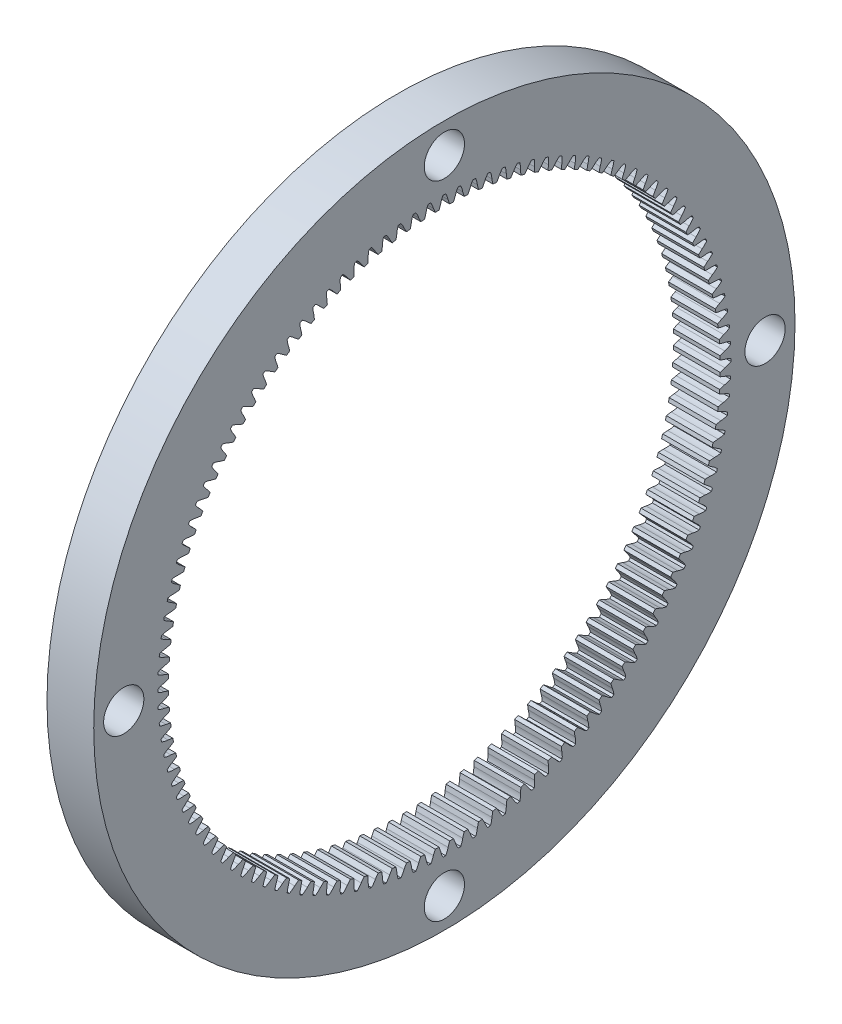
SolidWorks part; units mm, degrees
ref_plane "Front Plane" through (0, 0, 0) normal (0, 0, 1) x (1, 0, 0)
ref_plane "Top Plane" through (0, 0, 0) normal (0, 1, 0) x (1, 0, 0)
ref_plane "Right Plane" through (0, 0, 0) normal (1, 0, 0) x (0, 0, -1)
ref_plane "Plane1" through (2.5, 0, 0) normal (1, 0, 0) x (0, 0, -1)
sketch "Sketch1" plane through (2.5, 0, 0) normal (1, 0, 0) x (0, 0, -1)
  line L0 (1.9621, 29.9358) -> (2.1111, 29.4244)
  line L1 (2.5178, 29.3924) -> (2.7451, 29.8741)
  line L2 (3.5261, 29.7921) -> (3.6482, 29.2735)
  line L3 (4.0527, 29.2203) -> (4.3048, 29.6895)
  line L4 (5.0805, 29.5667) -> (5.1753, 29.0425)
  line L5 (5.5764, 28.9682) -> (5.8527, 29.4236)
  line L6 (6.6209, 29.2603) -> (6.6881, 28.7318)
  line L7 (7.0848, 28.6366) -> (7.3846, 29.0769)
  line L8 (8.1432, 28.8737) -> (8.1827, 28.3424)
  line L9 (8.5738, 28.2266) -> (8.8963, 28.6506)
  line L10 (9.6432, 28.4079) -> (9.6548, 27.8753)
  line L11 (10.0393, 27.7392) -> (10.3835, 28.1457)
  line L12 (11.1167, 27.8643) -> (11.1004, 27.3319)
  line L13 (11.4773, 27.1757) -> (11.8423, 27.5637)
  line L14 (12.5598, 27.2443) -> (12.5157, 26.7134)
  line L15 (12.8839, 26.5378) -> (13.2687, 26.9062)
  line L16 (13.9684, 26.5496) -> (13.8966, 26.0218)
  line L17 (14.2551, 25.8272) -> (14.6586, 26.1749)
  line L18 (15.3388, 25.7822) -> (15.2394, 25.2589)
  line L19 (15.5873, 25.0457) -> (16.0084, 25.3718)
  line L20 (16.6671, 24.9441) -> (16.5405, 24.4267)
  line L21 (16.8767, 24.1956) -> (17.3144, 24.4992)
  line L22 (17.9497, 24.0376) -> (17.7962, 23.5275)
  line L23 (18.1199, 23.2792) -> (18.5728, 23.5595)
  line L24 (19.1832, 23.0653) -> (19.0032, 22.5639)
  line L25 (19.3134, 22.299) -> (19.7804, 22.5552)
  line L26 (20.364, 22.0297) -> (20.158, 21.5384)
  line L27 (20.4539, 21.2576) -> (20.9337, 21.4891)
  line L28 (21.4891, 20.9337) -> (21.2576, 20.4539)
  line L29 (21.5384, 20.158) -> (22.0297, 20.364)
  line L30 (22.5552, 19.7804) -> (22.299, 19.3134)
  line L31 (22.5639, 19.0032) -> (23.0653, 19.1832)
  line L32 (23.5595, 18.5728) -> (23.2792, 18.1199)
  line L33 (23.5275, 17.7962) -> (24.0376, 17.9497)
  line L34 (24.4992, 17.3144) -> (24.1956, 16.8767)
  line L35 (24.4267, 16.5405) -> (24.9441, 16.6671)
  line L36 (25.3718, 16.0084) -> (25.0457, 15.5873)
  line L37 (25.2589, 15.2394) -> (25.7822, 15.3388)
  line L38 (26.1749, 14.6586) -> (25.8272, 14.2551)
  line L39 (26.0218, 13.8966) -> (26.5496, 13.9684)
  line L40 (26.9062, 13.2687) -> (26.5378, 12.8839)
  line L41 (26.7134, 12.5157) -> (27.2443, 12.5598)
  line L42 (27.5637, 11.8423) -> (27.1757, 11.4773)
  line L43 (27.3319, 11.1004) -> (27.8643, 11.1167)
  line L44 (28.1457, 10.3835) -> (27.7392, 10.0393)
  line L45 (27.8753, 9.6548) -> (28.4079, 9.6432)
  line L46 (28.6506, 8.8963) -> (28.2266, 8.5738)
  line L47 (28.3424, 8.1827) -> (28.8737, 8.1432)
  line L48 (29.0769, 7.3846) -> (28.6366, 7.0848)
  line L49 (28.7318, 6.6881) -> (29.2603, 6.6209)
  line L50 (29.4236, 5.8527) -> (28.9682, 5.5764)
  line L51 (29.0425, 5.1753) -> (29.5667, 5.0805)
  line L52 (29.6895, 4.3048) -> (29.2203, 4.0527)
  line L53 (29.2735, 3.6482) -> (29.7921, 3.5261)
  line L54 (29.8741, 2.7451) -> (29.3924, 2.5178)
  line L55 (29.4244, 2.1111) -> (29.9358, 1.9621)
  line L56 (29.9769, 1.1778) -> (29.4838, 0.9761)
  line L57 (29.4945, 0.5683) -> (29.9974, 0.3927)
  line L58 (29.9974, -0.3927) -> (29.4945, -0.5683)
  line L59 (29.4838, -0.9761) -> (29.9769, -1.1778)
  line L60 (29.9358, -1.9621) -> (29.4244, -2.1111)
  line L61 (29.3924, -2.5178) -> (29.8741, -2.7451)
  line L62 (29.7921, -3.5261) -> (29.2735, -3.6482)
  line L63 (29.2203, -4.0527) -> (29.6895, -4.3048)
  line L64 (29.5667, -5.0805) -> (29.0425, -5.1753)
  line L65 (28.9682, -5.5764) -> (29.4236, -5.8527)
  line L66 (29.2603, -6.6209) -> (28.7318, -6.6881)
  line L67 (28.6366, -7.0848) -> (29.0769, -7.3846)
  line L68 (28.8737, -8.1432) -> (28.3424, -8.1827)
  line L69 (28.2266, -8.5738) -> (28.6506, -8.8963)
  line L70 (28.4079, -9.6432) -> (27.8753, -9.6548)
  line L71 (27.7392, -10.0393) -> (28.1457, -10.3835)
  line L72 (27.8643, -11.1167) -> (27.3319, -11.1004)
  line L73 (27.1757, -11.4773) -> (27.5637, -11.8423)
  line L74 (27.2443, -12.5598) -> (26.7134, -12.5157)
  line L75 (26.5378, -12.8839) -> (26.9062, -13.2687)
  line L76 (26.5496, -13.9684) -> (26.0218, -13.8966)
  line L77 (25.8272, -14.2551) -> (26.1749, -14.6586)
  line L78 (25.7822, -15.3388) -> (25.2589, -15.2394)
  line L79 (25.0457, -15.5873) -> (25.3718, -16.0084)
  line L80 (24.9441, -16.6671) -> (24.4267, -16.5405)
  line L81 (24.1956, -16.8767) -> (24.4992, -17.3144)
  line L82 (24.0376, -17.9497) -> (23.5275, -17.7962)
  line L83 (23.2792, -18.1199) -> (23.5595, -18.5728)
  line L84 (23.0653, -19.1832) -> (22.5639, -19.0032)
  line L85 (22.299, -19.3134) -> (22.5552, -19.7804)
  line L86 (22.0297, -20.364) -> (21.5384, -20.158)
  line L87 (21.2576, -20.4539) -> (21.4891, -20.9337)
  line L88 (20.9337, -21.4891) -> (20.4539, -21.2576)
  line L89 (20.158, -21.5384) -> (20.364, -22.0297)
  line L90 (19.7804, -22.5552) -> (19.3134, -22.299)
  line L91 (19.0032, -22.5639) -> (19.1832, -23.0653)
  line L92 (18.5728, -23.5595) -> (18.1199, -23.2792)
  line L93 (17.7962, -23.5275) -> (17.9497, -24.0376)
  line L94 (17.3144, -24.4992) -> (16.8767, -24.1956)
  line L95 (16.5405, -24.4267) -> (16.6671, -24.9441)
  line L96 (16.0084, -25.3718) -> (15.5873, -25.0457)
  line L97 (15.2394, -25.2589) -> (15.3388, -25.7822)
  line L98 (14.6586, -26.1749) -> (14.2551, -25.8272)
  line L99 (13.8966, -26.0218) -> (13.9684, -26.5496)
  line L100 (13.2687, -26.9062) -> (12.8839, -26.5378)
  line L101 (12.5157, -26.7134) -> (12.5598, -27.2443)
  line L102 (11.8423, -27.5637) -> (11.4773, -27.1757)
  line L103 (11.1004, -27.3319) -> (11.1167, -27.8643)
  line L104 (10.3835, -28.1457) -> (10.0393, -27.7392)
  line L105 (9.6548, -27.8753) -> (9.6432, -28.4079)
  line L106 (8.8963, -28.6506) -> (8.5738, -28.2266)
  line L107 (8.1827, -28.3424) -> (8.1432, -28.8737)
  line L108 (7.3846, -29.0769) -> (7.0848, -28.6366)
  line L109 (6.6881, -28.7318) -> (6.6209, -29.2603)
  line L110 (5.8527, -29.4236) -> (5.5764, -28.9682)
  line L111 (5.1753, -29.0425) -> (5.0805, -29.5667)
  line L112 (4.3048, -29.6895) -> (4.0527, -29.2203)
  line L113 (3.6482, -29.2735) -> (3.5261, -29.7921)
  line L114 (2.7451, -29.8741) -> (2.5178, -29.3924)
  line L115 (2.1111, -29.4244) -> (1.9621, -29.9358)
  line L116 (1.1778, -29.9769) -> (0.9761, -29.4838)
  line L117 (0.5683, -29.4945) -> (0.3927, -29.9974)
  line L118 (-0.3927, -29.9974) -> (-0.5683, -29.4945)
  line L119 (-0.9761, -29.4838) -> (-1.1778, -29.9769)
  line L120 (-1.9621, -29.9358) -> (-2.1111, -29.4244)
  line L121 (-2.5178, -29.3924) -> (-2.7451, -29.8741)
  line L122 (-3.5261, -29.7921) -> (-3.6482, -29.2735)
  line L123 (-4.0527, -29.2203) -> (-4.3048, -29.6895)
  line L124 (-5.0805, -29.5667) -> (-5.1753, -29.0425)
  line L125 (-5.5764, -28.9682) -> (-5.8527, -29.4236)
  line L126 (-6.6209, -29.2603) -> (-6.6881, -28.7318)
  line L127 (-7.0848, -28.6366) -> (-7.3846, -29.0769)
  line L128 (-8.1432, -28.8737) -> (-8.1827, -28.3424)
  line L129 (-8.5738, -28.2266) -> (-8.8963, -28.6506)
  line L130 (-9.6432, -28.4079) -> (-9.6548, -27.8753)
  line L131 (-10.0393, -27.7392) -> (-10.3835, -28.1457)
  line L132 (-11.1167, -27.8643) -> (-11.1004, -27.3319)
  line L133 (-11.4773, -27.1757) -> (-11.8423, -27.5637)
  line L134 (-12.5598, -27.2443) -> (-12.5157, -26.7134)
  line L135 (-12.8839, -26.5378) -> (-13.2687, -26.9062)
  line L136 (-13.9684, -26.5496) -> (-13.8966, -26.0218)
  line L137 (-14.2551, -25.8272) -> (-14.6586, -26.1749)
  line L138 (-15.3388, -25.7822) -> (-15.2394, -25.2589)
  line L139 (-15.5873, -25.0457) -> (-16.0084, -25.3718)
  line L140 (-16.6671, -24.9441) -> (-16.5405, -24.4267)
  line L141 (-16.8767, -24.1956) -> (-17.3144, -24.4992)
  line L142 (-17.9497, -24.0376) -> (-17.7962, -23.5275)
  line L143 (-18.1199, -23.2792) -> (-18.5728, -23.5595)
  line L144 (-19.1832, -23.0653) -> (-19.0032, -22.5639)
  line L145 (-19.3134, -22.299) -> (-19.7804, -22.5552)
  line L146 (-20.364, -22.0297) -> (-20.158, -21.5384)
  line L147 (-20.4539, -21.2576) -> (-20.9337, -21.4891)
  line L148 (-21.4891, -20.9337) -> (-21.2576, -20.4539)
  line L149 (-21.5384, -20.158) -> (-22.0297, -20.364)
  line L150 (-22.5552, -19.7804) -> (-22.299, -19.3134)
  line L151 (-22.5639, -19.0032) -> (-23.0653, -19.1832)
  line L152 (-23.5595, -18.5728) -> (-23.2792, -18.1199)
  line L153 (-23.5275, -17.7962) -> (-24.0376, -17.9497)
  line L154 (-24.4992, -17.3144) -> (-24.1956, -16.8767)
  line L155 (-24.4267, -16.5405) -> (-24.9441, -16.6671)
  line L156 (-25.3718, -16.0084) -> (-25.0457, -15.5873)
  line L157 (-25.2589, -15.2394) -> (-25.7822, -15.3388)
  line L158 (-26.1749, -14.6586) -> (-25.8272, -14.2551)
  line L159 (-26.0218, -13.8966) -> (-26.5496, -13.9684)
  line L160 (-26.9062, -13.2687) -> (-26.5378, -12.8839)
  line L161 (-26.7134, -12.5157) -> (-27.2443, -12.5598)
  line L162 (-27.5637, -11.8423) -> (-27.1757, -11.4773)
  line L163 (-27.3319, -11.1004) -> (-27.8643, -11.1167)
  line L164 (-28.1457, -10.3835) -> (-27.7392, -10.0393)
  line L165 (-27.8753, -9.6548) -> (-28.4079, -9.6432)
  line L166 (-28.6506, -8.8963) -> (-28.2266, -8.5738)
  line L167 (-28.3424, -8.1827) -> (-28.8737, -8.1432)
  line L168 (-29.0769, -7.3846) -> (-28.6366, -7.0848)
  line L169 (-28.7318, -6.6881) -> (-29.2603, -6.6209)
  line L170 (-29.4236, -5.8527) -> (-28.9682, -5.5764)
  line L171 (-29.0425, -5.1753) -> (-29.5667, -5.0805)
  line L172 (-29.6895, -4.3048) -> (-29.2203, -4.0527)
  line L173 (-29.2735, -3.6482) -> (-29.7921, -3.5261)
  line L174 (-29.8741, -2.7451) -> (-29.3924, -2.5178)
  line L175 (-29.4244, -2.1111) -> (-29.9358, -1.9621)
  line L176 (-29.9769, -1.1778) -> (-29.4838, -0.9761)
  line L177 (-29.4945, -0.5683) -> (-29.9974, -0.3927)
  line L178 (-29.9974, 0.3927) -> (-29.4945, 0.5683)
  line L179 (-29.4838, 0.9761) -> (-29.9769, 1.1778)
  line L180 (-29.9358, 1.9621) -> (-29.4244, 2.1111)
  line L181 (-29.3924, 2.5178) -> (-29.8741, 2.7451)
  line L182 (-29.7921, 3.5261) -> (-29.2735, 3.6482)
  line L183 (-29.2203, 4.0527) -> (-29.6895, 4.3048)
  line L184 (-29.5667, 5.0805) -> (-29.0425, 5.1753)
  line L185 (-28.9682, 5.5764) -> (-29.4236, 5.8527)
  line L186 (-29.2603, 6.6209) -> (-28.7318, 6.6881)
  line L187 (-28.6366, 7.0848) -> (-29.0769, 7.3846)
  line L188 (-28.8737, 8.1432) -> (-28.3424, 8.1827)
  line L189 (-28.2266, 8.5738) -> (-28.6506, 8.8963)
  line L190 (-28.4079, 9.6432) -> (-27.8753, 9.6548)
  line L191 (-27.7392, 10.0393) -> (-28.1457, 10.3835)
  line L192 (-27.8643, 11.1167) -> (-27.3319, 11.1004)
  line L193 (-27.1757, 11.4773) -> (-27.5637, 11.8423)
  line L194 (-27.2443, 12.5598) -> (-26.7134, 12.5157)
  line L195 (-26.5378, 12.8839) -> (-26.9062, 13.2687)
  line L196 (-26.5496, 13.9684) -> (-26.0218, 13.8966)
  line L197 (-25.8272, 14.2551) -> (-26.1749, 14.6586)
  line L198 (-25.7822, 15.3388) -> (-25.2589, 15.2394)
  line L199 (-25.0457, 15.5873) -> (-25.3718, 16.0084)
  line L200 (-24.9441, 16.6671) -> (-24.4267, 16.5405)
  line L201 (-24.1956, 16.8767) -> (-24.4992, 17.3144)
  line L202 (-24.0376, 17.9497) -> (-23.5275, 17.7962)
  line L203 (-23.2792, 18.1199) -> (-23.5595, 18.5728)
  line L204 (-23.0653, 19.1832) -> (-22.5639, 19.0032)
  line L205 (-22.299, 19.3134) -> (-22.5552, 19.7804)
  line L206 (-22.0297, 20.364) -> (-21.5384, 20.158)
  line L207 (-21.2576, 20.4539) -> (-21.4891, 20.9337)
  line L208 (-20.9337, 21.4891) -> (-20.4539, 21.2576)
  line L209 (-20.158, 21.5384) -> (-20.364, 22.0297)
  line L210 (-19.7804, 22.5552) -> (-19.3134, 22.299)
  line L211 (-19.0032, 22.5639) -> (-19.1832, 23.0653)
  line L212 (-18.5728, 23.5595) -> (-18.1199, 23.2792)
  line L213 (-17.7962, 23.5275) -> (-17.9497, 24.0376)
  line L214 (-17.3144, 24.4992) -> (-16.8767, 24.1956)
  line L215 (-16.5405, 24.4267) -> (-16.6671, 24.9441)
  line L216 (-16.0084, 25.3718) -> (-15.5873, 25.0457)
  line L217 (-15.2394, 25.2589) -> (-15.3388, 25.7822)
  line L218 (-14.6586, 26.1749) -> (-14.2551, 25.8272)
  line L219 (-13.8966, 26.0218) -> (-13.9684, 26.5496)
  line L220 (-13.2687, 26.9062) -> (-12.8839, 26.5378)
  line L221 (-12.5157, 26.7134) -> (-12.5598, 27.2443)
  line L222 (-11.8423, 27.5637) -> (-11.4773, 27.1757)
  line L223 (-11.1004, 27.3319) -> (-11.1167, 27.8643)
  line L224 (-10.3835, 28.1457) -> (-10.0393, 27.7392)
  line L225 (-9.6548, 27.8753) -> (-9.6432, 28.4079)
  line L226 (-8.8963, 28.6506) -> (-8.5738, 28.2266)
  line L227 (-8.1827, 28.3424) -> (-8.1432, 28.8737)
  line L228 (-7.3846, 29.0769) -> (-7.0848, 28.6366)
  line L229 (-6.6881, 28.7318) -> (-6.6209, 29.2603)
  line L230 (-5.8527, 29.4236) -> (-5.5764, 28.9682)
  line L231 (-5.1753, 29.0425) -> (-5.0805, 29.5667)
  line L232 (-4.3048, 29.6895) -> (-4.0527, 29.2203)
  line L233 (-3.6482, 29.2735) -> (-3.5261, 29.7921)
  line L234 (-2.7451, 29.8741) -> (-2.5178, 29.3924)
  line L235 (-2.1111, 29.4244) -> (-1.9621, 29.9358)
  line L236 (-1.1778, 29.9769) -> (-0.9761, 29.4838)
  line L237 (-0.5683, 29.4945) -> (-0.3927, 29.9974)
  line L238 (0.3927, 29.9974) -> (0.5683, 29.4945)
  line L239 (0.9761, 29.4838) -> (1.1778, 29.9769)
  arc A0 (1.4636, 30.6158) -> (1.7447, 30.6011) centre (0, 0) cw
  arc A1 (2.1111, 29.4244) -> (2.5178, 29.3924) centre (0, 0) cw
  arc A2 (3.0639, 30.4973) -> (3.3438, 30.4679) centre (0, 0) cw
  arc A3 (3.6482, 29.2735) -> (4.0527, 29.2203) centre (0, 0) cw
  arc A4 (4.6558, 30.2951) -> (4.9338, 30.2511) centre (0, 0) cw
  arc A5 (5.1753, 29.0425) -> (5.5764, 28.9682) centre (0, 0) cw
  arc A6 (6.2349, 30.01) -> (6.5103, 29.9514) centre (0, 0) cw
  arc A7 (6.6881, 28.7318) -> (7.0848, 28.6366) centre (0, 0) cw
  arc A8 (7.797, 29.6425) -> (8.0689, 29.5697) centre (0, 0) cw
  arc A9 (8.1827, 28.3424) -> (8.5738, 28.2266) centre (0, 0) cw
  arc A10 (9.3377, 29.1938) -> (9.6054, 29.1068) centre (0, 0) cw
  arc A11 (9.6548, 27.8753) -> (10.0393, 27.7392) centre (0, 0) cw
  arc A12 (10.8528, 28.6651) -> (11.1155, 28.5642) centre (0, 0) cw
  arc A13 (11.1004, 27.3319) -> (11.4773, 27.1757) centre (0, 0) cw
  arc A14 (12.3381, 28.0578) -> (12.5952, 27.9434) centre (0, 0) cw
  arc A15 (12.5157, 26.7134) -> (12.8839, 26.5378) centre (0, 0) cw
  arc A16 (13.7896, 27.3737) -> (14.0404, 27.2459) centre (0, 0) cw
  arc A17 (13.8966, 26.0218) -> (14.2551, 25.8272) centre (0, 0) cw
  arc A18 (15.2034, 26.6145) -> (15.4471, 26.4737) centre (0, 0) cw
  arc A19 (15.2394, 25.2589) -> (15.5873, 25.0457) centre (0, 0) cw
  arc A20 (16.5754, 25.7823) -> (16.8115, 25.629) centre (0, 0) cw
  arc A21 (16.5405, 24.4267) -> (16.8767, 24.1956) centre (0, 0) cw
  arc A22 (17.902, 24.8795) -> (18.1298, 24.714) centre (0, 0) cw
  arc A23 (17.7962, 23.5275) -> (18.1199, 23.2792) centre (0, 0) cw
  arc A24 (19.1796, 23.9085) -> (19.3983, 23.7313) centre (0, 0) cw
  arc A25 (19.0032, 22.5639) -> (19.3134, 22.299) centre (0, 0) cw
  arc A26 (20.4046, 22.8719) -> (20.6138, 22.6836) centre (0, 0) cw
  arc A27 (20.158, 21.5384) -> (20.4539, 21.2576) centre (0, 0) cw
  arc A28 (21.5736, 21.7727) -> (21.7727, 21.5736) centre (0, 0) cw
  arc A29 (21.2576, 20.4539) -> (21.5384, 20.158) centre (0, 0) cw
  arc A30 (22.6836, 20.6138) -> (22.8719, 20.4046) centre (0, 0) cw
  arc A31 (22.299, 19.3134) -> (22.5639, 19.0032) centre (0, 0) cw
  arc A32 (23.7313, 19.3983) -> (23.9085, 19.1796) centre (0, 0) cw
  arc A33 (23.2792, 18.1199) -> (23.5275, 17.7962) centre (0, 0) cw
  arc A34 (24.714, 18.1298) -> (24.8795, 17.902) centre (0, 0) cw
  arc A35 (24.1956, 16.8767) -> (24.4267, 16.5405) centre (0, 0) cw
  arc A36 (25.629, 16.8115) -> (25.7823, 16.5754) centre (0, 0) cw
  arc A37 (25.0457, 15.5873) -> (25.2589, 15.2394) centre (0, 0) cw
  arc A38 (26.4737, 15.4471) -> (26.6145, 15.2034) centre (0, 0) cw
  arc A39 (25.8272, 14.2551) -> (26.0218, 13.8966) centre (0, 0) cw
  arc A40 (27.2459, 14.0404) -> (27.3737, 13.7896) centre (0, 0) cw
  arc A41 (26.5378, 12.8839) -> (26.7134, 12.5157) centre (0, 0) cw
  arc A42 (27.9434, 12.5952) -> (28.0578, 12.3381) centre (0, 0) cw
  arc A43 (27.1757, 11.4773) -> (27.3319, 11.1004) centre (0, 0) cw
  arc A44 (28.5642, 11.1155) -> (28.6651, 10.8528) centre (0, 0) cw
  arc A45 (27.7392, 10.0393) -> (27.8753, 9.6548) centre (0, 0) cw
  arc A46 (29.1068, 9.6054) -> (29.1938, 9.3377) centre (0, 0) cw
  arc A47 (28.2266, 8.5738) -> (28.3424, 8.1827) centre (0, 0) cw
  arc A48 (29.5697, 8.0689) -> (29.6425, 7.797) centre (0, 0) cw
  arc A49 (28.6366, 7.0848) -> (28.7318, 6.6881) centre (0, 0) cw
  arc A50 (29.9514, 6.5103) -> (30.01, 6.2349) centre (0, 0) cw
  arc A51 (28.9682, 5.5764) -> (29.0425, 5.1753) centre (0, 0) cw
  arc A52 (30.2511, 4.9338) -> (30.2951, 4.6558) centre (0, 0) cw
  arc A53 (29.2203, 4.0527) -> (29.2735, 3.6482) centre (0, 0) cw
  arc A54 (30.4679, 3.3438) -> (30.4973, 3.0639) centre (0, 0) cw
  arc A55 (29.3924, 2.5178) -> (29.4244, 2.1111) centre (0, 0) cw
  arc A56 (30.6011, 1.7447) -> (30.6158, 1.4636) centre (0, 0) cw
  arc A57 (29.4838, 0.9761) -> (29.4945, 0.5683) centre (0, 0) cw
  arc A58 (30.6505, 0.1407) -> (30.6505, -0.1407) centre (0, 0) cw
  arc A59 (29.4945, -0.5683) -> (29.4838, -0.9761) centre (0, 0) cw
  arc A60 (30.6158, -1.4636) -> (30.6011, -1.7447) centre (0, 0) cw
  arc A61 (29.4244, -2.1111) -> (29.3924, -2.5178) centre (0, 0) cw
  arc A62 (30.4973, -3.0639) -> (30.4679, -3.3438) centre (0, 0) cw
  arc A63 (29.2735, -3.6482) -> (29.2203, -4.0527) centre (0, 0) cw
  arc A64 (30.2951, -4.6558) -> (30.2511, -4.9338) centre (0, 0) cw
  arc A65 (29.0425, -5.1753) -> (28.9682, -5.5764) centre (0, 0) cw
  arc A66 (30.01, -6.2349) -> (29.9514, -6.5103) centre (0, 0) cw
  arc A67 (28.7318, -6.6881) -> (28.6366, -7.0848) centre (0, 0) cw
  arc A68 (29.6425, -7.797) -> (29.5697, -8.0689) centre (0, 0) cw
  arc A69 (28.3424, -8.1827) -> (28.2266, -8.5738) centre (0, 0) cw
  arc A70 (29.1938, -9.3377) -> (29.1068, -9.6054) centre (0, 0) cw
  arc A71 (27.8753, -9.6548) -> (27.7392, -10.0393) centre (0, 0) cw
  arc A72 (28.6651, -10.8528) -> (28.5642, -11.1155) centre (0, 0) cw
  arc A73 (27.3319, -11.1004) -> (27.1757, -11.4773) centre (0, 0) cw
  arc A74 (28.0578, -12.3381) -> (27.9434, -12.5952) centre (0, 0) cw
  arc A75 (26.7134, -12.5157) -> (26.5378, -12.8839) centre (0, 0) cw
  arc A76 (27.3737, -13.7896) -> (27.2459, -14.0404) centre (0, 0) cw
  arc A77 (26.0218, -13.8966) -> (25.8272, -14.2551) centre (0, 0) cw
  arc A78 (26.6145, -15.2034) -> (26.4737, -15.4471) centre (0, 0) cw
  arc A79 (25.2589, -15.2394) -> (25.0457, -15.5873) centre (0, 0) cw
  arc A80 (25.7823, -16.5754) -> (25.629, -16.8115) centre (0, 0) cw
  arc A81 (24.4267, -16.5405) -> (24.1956, -16.8767) centre (0, 0) cw
  arc A82 (24.8795, -17.902) -> (24.714, -18.1298) centre (0, 0) cw
  arc A83 (23.5275, -17.7962) -> (23.2792, -18.1199) centre (0, 0) cw
  arc A84 (23.9085, -19.1796) -> (23.7313, -19.3983) centre (0, 0) cw
  arc A85 (22.5639, -19.0032) -> (22.299, -19.3134) centre (0, 0) cw
  arc A86 (22.8719, -20.4046) -> (22.6836, -20.6138) centre (0, 0) cw
  arc A87 (21.5384, -20.158) -> (21.2576, -20.4539) centre (0, 0) cw
  arc A88 (21.7727, -21.5736) -> (21.5736, -21.7727) centre (0, 0) cw
  arc A89 (20.4539, -21.2576) -> (20.158, -21.5384) centre (0, 0) cw
  arc A90 (20.6138, -22.6836) -> (20.4046, -22.8719) centre (0, 0) cw
  arc A91 (19.3134, -22.299) -> (19.0032, -22.5639) centre (0, 0) cw
  arc A92 (19.3983, -23.7313) -> (19.1796, -23.9085) centre (0, 0) cw
  arc A93 (18.1199, -23.2792) -> (17.7962, -23.5275) centre (0, 0) cw
  arc A94 (18.1298, -24.714) -> (17.902, -24.8795) centre (0, 0) cw
  arc A95 (16.8767, -24.1956) -> (16.5405, -24.4267) centre (0, 0) cw
  arc A96 (16.8115, -25.629) -> (16.5754, -25.7823) centre (0, 0) cw
  arc A97 (15.5873, -25.0457) -> (15.2394, -25.2589) centre (0, 0) cw
  arc A98 (15.4471, -26.4737) -> (15.2034, -26.6145) centre (0, 0) cw
  arc A99 (14.2551, -25.8272) -> (13.8966, -26.0218) centre (0, 0) cw
  arc A100 (14.0404, -27.2459) -> (13.7896, -27.3737) centre (0, 0) cw
  arc A101 (12.8839, -26.5378) -> (12.5157, -26.7134) centre (0, 0) cw
  arc A102 (12.5952, -27.9434) -> (12.3381, -28.0578) centre (0, 0) cw
  arc A103 (11.4773, -27.1757) -> (11.1004, -27.3319) centre (0, 0) cw
  arc A104 (11.1155, -28.5642) -> (10.8528, -28.6651) centre (0, 0) cw
  arc A105 (10.0393, -27.7392) -> (9.6548, -27.8753) centre (0, 0) cw
  arc A106 (9.6054, -29.1068) -> (9.3377, -29.1938) centre (0, 0) cw
  arc A107 (8.5738, -28.2266) -> (8.1827, -28.3424) centre (0, 0) cw
  arc A108 (8.0689, -29.5697) -> (7.797, -29.6425) centre (0, 0) cw
  arc A109 (7.0848, -28.6366) -> (6.6881, -28.7318) centre (0, 0) cw
  arc A110 (6.5103, -29.9514) -> (6.2349, -30.01) centre (0, 0) cw
  arc A111 (5.5764, -28.9682) -> (5.1753, -29.0425) centre (0, 0) cw
  arc A112 (4.9338, -30.2511) -> (4.6558, -30.2951) centre (0, 0) cw
  arc A113 (4.0527, -29.2203) -> (3.6482, -29.2735) centre (0, 0) cw
  arc A114 (3.3438, -30.4679) -> (3.0639, -30.4973) centre (0, 0) cw
  arc A115 (2.5178, -29.3924) -> (2.1111, -29.4244) centre (0, 0) cw
  arc A116 (1.7447, -30.6011) -> (1.4636, -30.6158) centre (0, 0) cw
  arc A117 (0.9761, -29.4838) -> (0.5683, -29.4945) centre (0, 0) cw
  arc A118 (0.1407, -30.6505) -> (-0.1407, -30.6505) centre (0, 0) cw
  arc A119 (-0.5683, -29.4945) -> (-0.9761, -29.4838) centre (0, 0) cw
  arc A120 (-1.4636, -30.6158) -> (-1.7447, -30.6011) centre (0, 0) cw
  arc A121 (-2.1111, -29.4244) -> (-2.5178, -29.3924) centre (0, 0) cw
  arc A122 (-3.0639, -30.4973) -> (-3.3438, -30.4679) centre (0, 0) cw
  arc A123 (-3.6482, -29.2735) -> (-4.0527, -29.2203) centre (0, 0) cw
  arc A124 (-4.6558, -30.2951) -> (-4.9338, -30.2511) centre (0, 0) cw
  arc A125 (-5.1753, -29.0425) -> (-5.5764, -28.9682) centre (0, 0) cw
  arc A126 (-6.2349, -30.01) -> (-6.5103, -29.9514) centre (0, 0) cw
  arc A127 (-6.6881, -28.7318) -> (-7.0848, -28.6366) centre (0, 0) cw
  arc A128 (-7.797, -29.6425) -> (-8.0689, -29.5697) centre (0, 0) cw
  arc A129 (-8.1827, -28.3424) -> (-8.5738, -28.2266) centre (0, 0) cw
  arc A130 (-9.3377, -29.1938) -> (-9.6054, -29.1068) centre (0, 0) cw
  arc A131 (-9.6548, -27.8753) -> (-10.0393, -27.7392) centre (0, 0) cw
  arc A132 (-10.8528, -28.6651) -> (-11.1155, -28.5642) centre (0, 0) cw
  arc A133 (-11.1004, -27.3319) -> (-11.4773, -27.1757) centre (0, 0) cw
  arc A134 (-12.3381, -28.0578) -> (-12.5952, -27.9434) centre (0, 0) cw
  arc A135 (-12.5157, -26.7134) -> (-12.8839, -26.5378) centre (0, 0) cw
  arc A136 (-13.7896, -27.3737) -> (-14.0404, -27.2459) centre (0, 0) cw
  arc A137 (-13.8966, -26.0218) -> (-14.2551, -25.8272) centre (0, 0) cw
  arc A138 (-15.2034, -26.6145) -> (-15.4471, -26.4737) centre (0, 0) cw
  arc A139 (-15.2394, -25.2589) -> (-15.5873, -25.0457) centre (0, 0) cw
  arc A140 (-16.5754, -25.7823) -> (-16.8115, -25.629) centre (0, 0) cw
  arc A141 (-16.5405, -24.4267) -> (-16.8767, -24.1956) centre (0, 0) cw
  arc A142 (-17.902, -24.8795) -> (-18.1298, -24.714) centre (0, 0) cw
  arc A143 (-17.7962, -23.5275) -> (-18.1199, -23.2792) centre (0, 0) cw
  arc A144 (-19.1796, -23.9085) -> (-19.3983, -23.7313) centre (0, 0) cw
  arc A145 (-19.0032, -22.5639) -> (-19.3134, -22.299) centre (0, 0) cw
  arc A146 (-20.4046, -22.8719) -> (-20.6138, -22.6836) centre (0, 0) cw
  arc A147 (-20.158, -21.5384) -> (-20.4539, -21.2576) centre (0, 0) cw
  arc A148 (-21.5736, -21.7727) -> (-21.7727, -21.5736) centre (0, 0) cw
  arc A149 (-21.2576, -20.4539) -> (-21.5384, -20.158) centre (0, 0) cw
  arc A150 (-22.6836, -20.6138) -> (-22.8719, -20.4046) centre (0, 0) cw
  arc A151 (-22.299, -19.3134) -> (-22.5639, -19.0032) centre (0, 0) cw
  arc A152 (-23.7313, -19.3983) -> (-23.9085, -19.1796) centre (0, 0) cw
  arc A153 (-23.2792, -18.1199) -> (-23.5275, -17.7962) centre (0, 0) cw
  arc A154 (-24.714, -18.1298) -> (-24.8795, -17.902) centre (0, 0) cw
  arc A155 (-24.1956, -16.8767) -> (-24.4267, -16.5405) centre (0, 0) cw
  arc A156 (-25.629, -16.8115) -> (-25.7823, -16.5754) centre (0, 0) cw
  arc A157 (-25.0457, -15.5873) -> (-25.2589, -15.2394) centre (0, 0) cw
  arc A158 (-26.4737, -15.4471) -> (-26.6145, -15.2034) centre (0, 0) cw
  arc A159 (-25.8272, -14.2551) -> (-26.0218, -13.8966) centre (0, 0) cw
  arc A160 (-27.2459, -14.0404) -> (-27.3737, -13.7896) centre (0, 0) cw
  arc A161 (-26.5378, -12.8839) -> (-26.7134, -12.5157) centre (0, 0) cw
  arc A162 (-27.9434, -12.5952) -> (-28.0578, -12.3381) centre (0, 0) cw
  arc A163 (-27.1757, -11.4773) -> (-27.3319, -11.1004) centre (0, 0) cw
  arc A164 (-28.5642, -11.1155) -> (-28.6651, -10.8528) centre (0, 0) cw
  arc A165 (-27.7392, -10.0393) -> (-27.8753, -9.6548) centre (0, 0) cw
  arc A166 (-29.1068, -9.6054) -> (-29.1938, -9.3377) centre (0, 0) cw
  arc A167 (-28.2266, -8.5738) -> (-28.3424, -8.1827) centre (0, 0) cw
  arc A168 (-29.5697, -8.0689) -> (-29.6425, -7.797) centre (0, 0) cw
  arc A169 (-28.6366, -7.0848) -> (-28.7318, -6.6881) centre (0, 0) cw
  arc A170 (-29.9514, -6.5103) -> (-30.01, -6.2349) centre (0, 0) cw
  arc A171 (-28.9682, -5.5764) -> (-29.0425, -5.1753) centre (0, 0) cw
  arc A172 (-30.2511, -4.9338) -> (-30.2951, -4.6558) centre (0, 0) cw
  arc A173 (-29.2203, -4.0527) -> (-29.2735, -3.6482) centre (0, 0) cw
  arc A174 (-30.4679, -3.3438) -> (-30.4973, -3.0639) centre (0, 0) cw
  arc A175 (-29.3924, -2.5178) -> (-29.4244, -2.1111) centre (0, 0) cw
  arc A176 (-30.6011, -1.7447) -> (-30.6158, -1.4636) centre (0, 0) cw
  arc A177 (-29.4838, -0.9761) -> (-29.4945, -0.5683) centre (0, 0) cw
  arc A178 (-30.6505, -0.1407) -> (-30.6505, 0.1407) centre (0, 0) cw
  arc A179 (-29.4945, 0.5683) -> (-29.4838, 0.9761) centre (0, 0) cw
  arc A180 (-30.6158, 1.4636) -> (-30.6011, 1.7447) centre (0, 0) cw
  arc A181 (-29.4244, 2.1111) -> (-29.3924, 2.5178) centre (0, 0) cw
  arc A182 (-30.4973, 3.0639) -> (-30.4679, 3.3438) centre (0, 0) cw
  arc A183 (-29.2735, 3.6482) -> (-29.2203, 4.0527) centre (0, 0) cw
  arc A184 (-30.2951, 4.6558) -> (-30.2511, 4.9338) centre (0, 0) cw
  arc A185 (-29.0425, 5.1753) -> (-28.9682, 5.5764) centre (0, 0) cw
  arc A186 (-30.01, 6.2349) -> (-29.9514, 6.5103) centre (0, 0) cw
  arc A187 (-28.7318, 6.6881) -> (-28.6366, 7.0848) centre (0, 0) cw
  arc A188 (-29.6425, 7.797) -> (-29.5697, 8.0689) centre (0, 0) cw
  arc A189 (-28.3424, 8.1827) -> (-28.2266, 8.5738) centre (0, 0) cw
  arc A190 (-29.1938, 9.3377) -> (-29.1068, 9.6054) centre (0, 0) cw
  arc A191 (-27.8753, 9.6548) -> (-27.7392, 10.0393) centre (0, 0) cw
  arc A192 (-28.6651, 10.8528) -> (-28.5642, 11.1155) centre (0, 0) cw
  arc A193 (-27.3319, 11.1004) -> (-27.1757, 11.4773) centre (0, 0) cw
  arc A194 (-28.0578, 12.3381) -> (-27.9434, 12.5952) centre (0, 0) cw
  arc A195 (-26.7134, 12.5157) -> (-26.5378, 12.8839) centre (0, 0) cw
  arc A196 (-27.3737, 13.7896) -> (-27.2459, 14.0404) centre (0, 0) cw
  arc A197 (-26.0218, 13.8966) -> (-25.8272, 14.2551) centre (0, 0) cw
  arc A198 (-26.6145, 15.2034) -> (-26.4737, 15.4471) centre (0, 0) cw
  arc A199 (-25.2589, 15.2394) -> (-25.0457, 15.5873) centre (0, 0) cw
  arc A200 (-25.7823, 16.5754) -> (-25.629, 16.8115) centre (0, 0) cw
  arc A201 (-24.4267, 16.5405) -> (-24.1956, 16.8767) centre (0, 0) cw
  arc A202 (-24.8795, 17.902) -> (-24.714, 18.1298) centre (0, 0) cw
  arc A203 (-23.5275, 17.7962) -> (-23.2792, 18.1199) centre (0, 0) cw
  arc A204 (-23.9085, 19.1796) -> (-23.7313, 19.3983) centre (0, 0) cw
  arc A205 (-22.5639, 19.0032) -> (-22.299, 19.3134) centre (0, 0) cw
  arc A206 (-22.8719, 20.4046) -> (-22.6836, 20.6138) centre (0, 0) cw
  arc A207 (-21.5384, 20.158) -> (-21.2576, 20.4539) centre (0, 0) cw
  arc A208 (-21.7727, 21.5736) -> (-21.5736, 21.7727) centre (0, 0) cw
  arc A209 (-20.4539, 21.2576) -> (-20.158, 21.5384) centre (0, 0) cw
  arc A210 (-20.6138, 22.6836) -> (-20.4046, 22.8719) centre (0, 0) cw
  arc A211 (-19.3134, 22.299) -> (-19.0032, 22.5639) centre (0, 0) cw
  arc A212 (-19.3983, 23.7313) -> (-19.1796, 23.9085) centre (0, 0) cw
  arc A213 (-18.1199, 23.2792) -> (-17.7962, 23.5275) centre (0, 0) cw
  arc A214 (-18.1298, 24.714) -> (-17.902, 24.8795) centre (0, 0) cw
  arc A215 (-16.8767, 24.1956) -> (-16.5405, 24.4267) centre (0, 0) cw
  arc A216 (-16.8115, 25.629) -> (-16.5754, 25.7823) centre (0, 0) cw
  arc A217 (-15.5873, 25.0457) -> (-15.2394, 25.2589) centre (0, 0) cw
  arc A218 (-15.4471, 26.4737) -> (-15.2034, 26.6145) centre (0, 0) cw
  arc A219 (-14.2551, 25.8272) -> (-13.8966, 26.0218) centre (0, 0) cw
  arc A220 (-14.0404, 27.2459) -> (-13.7896, 27.3737) centre (0, 0) cw
  arc A221 (-12.8839, 26.5378) -> (-12.5157, 26.7134) centre (0, 0) cw
  arc A222 (-12.5952, 27.9434) -> (-12.3381, 28.0578) centre (0, 0) cw
  arc A223 (-11.4773, 27.1757) -> (-11.1004, 27.3319) centre (0, 0) cw
  arc A224 (-11.1155, 28.5642) -> (-10.8528, 28.6651) centre (0, 0) cw
  arc A225 (-10.0393, 27.7392) -> (-9.6548, 27.8753) centre (0, 0) cw
  arc A226 (-9.6054, 29.1068) -> (-9.3377, 29.1938) centre (0, 0) cw
  arc A227 (-8.5738, 28.2266) -> (-8.1827, 28.3424) centre (0, 0) cw
  arc A228 (-8.0689, 29.5697) -> (-7.797, 29.6425) centre (0, 0) cw
  arc A229 (-7.0848, 28.6366) -> (-6.6881, 28.7318) centre (0, 0) cw
  arc A230 (-6.5103, 29.9514) -> (-6.2349, 30.01) centre (0, 0) cw
  arc A231 (-5.5764, 28.9682) -> (-5.1753, 29.0425) centre (0, 0) cw
  arc A232 (-4.9338, 30.2511) -> (-4.6558, 30.2951) centre (0, 0) cw
  arc A233 (-4.0527, 29.2203) -> (-3.6482, 29.2735) centre (0, 0) cw
  arc A234 (-3.3438, 30.4679) -> (-3.0639, 30.4973) centre (0, 0) cw
  arc A235 (-2.5178, 29.3924) -> (-2.1111, 29.4244) centre (0, 0) cw
  arc A236 (-1.7447, 30.6011) -> (-1.4636, 30.6158) centre (0, 0) cw
  arc A237 (-0.9761, 29.4838) -> (-0.5683, 29.4945) centre (0, 0) cw
  arc A238 (-0.1407, 30.6505) -> (0.1407, 30.6505) centre (0, 0) cw
  arc A239 (0.5683, 29.4945) -> (0.9761, 29.4838) centre (0, 0) cw
  circle A240 centre (0, 0) radius 37.5
  spline S0 degree 3 poles (1.1778, 29.9769) (1.1943, 30.0479) (1.2168, 30.1177) (1.2429, 30.1858) (1.2717, 30.2607) (1.3051, 30.3339) (1.3419, 30.4052) (1.3791, 30.4772) (1.4199, 30.5475) (1.4636, 30.6158) knots 0 0 0 0 0.000219 0.000219 0.000219 0.000459 0.000459 0.000459 0.000703 0.000703 0.000703 0.000703
  spline S1 degree 3 poles (1.7447, 30.6011) (1.7753, 30.5379) (1.8037, 30.4735) (1.8297, 30.4082) (1.8556, 30.3429) (1.879, 30.2765) (1.8994, 30.2093) (1.9265, 30.1198) (1.9483, 30.0283) (1.9621, 29.9358) knots 0 0 0 0 0.000211 0.000211 0.000211 0.000422 0.000422 0.000422 0.000703 0.000703 0.000703 0.000703
  spline S2 degree 3 poles (2.7451, 29.8741) (2.7653, 29.9443) (2.7914, 30.0128) (2.821, 30.0794) (2.8536, 30.1527) (2.8908, 30.2241) (2.9313, 30.2933) (2.9723, 30.3633) (3.0167, 30.4313) (3.0639, 30.4973) knots 0 0 0 0 0.000219 0.000219 0.000219 0.000459 0.000459 0.000459 0.000703 0.000703 0.000703 0.000703
  spline S3 degree 3 poles (3.3438, 30.4679) (3.3711, 30.4031) (3.3961, 30.3374) (3.4186, 30.2708) (3.4411, 30.2042) (3.461, 30.1367) (3.4778, 30.0685) (3.5002, 29.9777) (3.5172, 29.8852) (3.5261, 29.7921) knots 0 0 0 0 0.000211 0.000211 0.000211 0.000422 0.000422 0.000422 0.000703 0.000703 0.000703 0.000703
  spline S4 degree 3 poles (4.3048, 29.6895) (4.3287, 29.7585) (4.3583, 29.8255) (4.3914, 29.8906) (4.4278, 29.962) (4.4687, 30.0313) (4.5128, 30.0984) (4.5573, 30.1661) (4.6052, 30.2317) (4.6558, 30.2951) knots 0 0 0 0 0.000219 0.000219 0.000219 0.000459 0.000459 0.000459 0.000703 0.000703 0.000703 0.000703
  spline S5 degree 3 poles (4.9338, 30.2511) (4.9576, 30.185) (4.9792, 30.1181) (4.9982, 30.0504) (5.0171, 29.9827) (5.0335, 29.9143) (5.0467, 29.8453) (5.0643, 29.7534) (5.0765, 29.6601) (5.0805, 29.5667) knots 0 0 0 0 0.000211 0.000211 0.000211 0.000422 0.000422 0.000422 0.000703 0.000703 0.000703 0.000703
  spline S6 degree 3 poles (5.8527, 29.4236) (5.8802, 29.4912) (5.9133, 29.5566) (5.9497, 29.6198) (5.9898, 29.6893) (6.0343, 29.7563) (6.0818, 29.8209) (6.1298, 29.8863) (6.1811, 29.9493) (6.2349, 30.01) knots 0 0 0 0 0.000219 0.000219 0.000219 0.000459 0.000459 0.000459 0.000703 0.000703 0.000703 0.000703
  spline S7 degree 3 poles (6.5103, 29.9514) (6.5306, 29.8842) (6.5486, 29.8162) (6.564, 29.7476) (6.5794, 29.6791) (6.5922, 29.6098) (6.6018, 29.5402) (6.6145, 29.4476) (6.6218, 29.3538) (6.6209, 29.2603) knots 0 0 0 0 0.000211 0.000211 0.000211 0.000422 0.000422 0.000422 0.000703 0.000703 0.000703 0.000703
  spline S8 degree 3 poles (7.3846, 29.0769) (7.4156, 29.143) (7.4521, 29.2066) (7.4918, 29.2678) (7.5354, 29.3351) (7.5833, 29.3997) (7.6342, 29.4618) (7.6855, 29.5245) (7.7401, 29.5847) (7.797, 29.6425) knots 0 0 0 0 0.000219 0.000219 0.000219 0.000459 0.000459 0.000459 0.000703 0.000703 0.000703 0.000703
  spline S9 degree 3 poles (8.0689, 29.5697) (8.0856, 29.5014) (8.1001, 29.4326) (8.1119, 29.3633) (8.1237, 29.2941) (8.1328, 29.2243) (8.1387, 29.1542) (8.1466, 29.061) (8.149, 28.967) (8.1432, 28.8737) knots 0 0 0 0 0.000211 0.000211 0.000211 0.000422 0.000422 0.000422 0.000703 0.000703 0.000703 0.000703
  spline S10 degree 3 poles (8.8963, 28.6506) (8.9306, 28.715) (8.9704, 28.7765) (9.0133, 28.8356) (9.0604, 28.9005) (9.1116, 28.9625) (9.1656, 29.0219) (9.2202, 29.0818) (9.2778, 29.1391) (9.3377, 29.1938) knots 0 0 0 0 0.000219 0.000219 0.000219 0.000459 0.000459 0.000459 0.000703 0.000703 0.000703 0.000703
  spline S11 degree 3 poles (9.6054, 29.1068) (9.6186, 29.0378) (9.6294, 28.9683) (9.6375, 28.8985) (9.6457, 28.8287) (9.6511, 28.7586) (9.6534, 28.6883) (9.6564, 28.5948) (9.6538, 28.5008) (9.6432, 28.4079) knots 0 0 0 0 0.000211 0.000211 0.000211 0.000422 0.000422 0.000422 0.000703 0.000703 0.000703 0.000703
  spline S12 degree 3 poles (10.3835, 28.1457) (10.4212, 28.2082) (10.4642, 28.2676) (10.51, 28.3244) (10.5605, 28.3867) (10.6149, 28.446) (10.6719, 28.5024) (10.7296, 28.5594) (10.7901, 28.6136) (10.8528, 28.6651) knots 0 0 0 0 0.000219 0.000219 0.000219 0.000459 0.000459 0.000459 0.000703 0.000703 0.000703 0.000703
  spline S13 degree 3 poles (11.1155, 28.5642) (11.1251, 28.4946) (11.1323, 28.4247) (11.1368, 28.3545) (11.1412, 28.2844) (11.143, 28.214) (11.1416, 28.1438) (11.1397, 28.0503) (11.1322, 27.9565) (11.1167, 27.8643) knots 0 0 0 0 0.000211 0.000211 0.000211 0.000422 0.000422 0.000422 0.000703 0.000703 0.000703 0.000703
  spline S14 degree 3 poles (11.8423, 27.5637) (11.8832, 27.6242) (11.9292, 27.6812) (11.978, 27.7355) (12.0317, 27.7951) (12.0891, 27.8515) (12.149, 27.9048) (12.2096, 27.9587) (12.2729, 28.0097) (12.3381, 28.0578) knots 0 0 0 0 0.000219 0.000219 0.000219 0.000459 0.000459 0.000459 0.000703 0.000703 0.000703 0.000703
  spline S15 degree 3 poles (12.5952, 27.9434) (12.6011, 27.8734) (12.6047, 27.8031) (12.6055, 27.7328) (12.6063, 27.6626) (12.6044, 27.5922) (12.5993, 27.5221) (12.5925, 27.4288) (12.5801, 27.3356) (12.5598, 27.2443) knots 0 0 0 0 0.000211 0.000211 0.000211 0.000422 0.000422 0.000422 0.000703 0.000703 0.000703 0.000703
  spline S16 degree 3 poles (13.2687, 26.9062) (13.3127, 26.9644) (13.3616, 27.019) (13.4132, 27.0706) (13.4699, 27.1273) (13.5302, 27.1806) (13.5928, 27.2307) (13.6561, 27.2814) (13.722, 27.329) (13.7896, 27.3737) knots 0 0 0 0 0.000219 0.000219 0.000219 0.000459 0.000459 0.000459 0.000703 0.000703 0.000703 0.000703
  spline S17 degree 3 poles (14.0404, 27.2459) (14.0427, 27.1757) (14.0425, 27.1053) (14.0396, 27.0351) (14.0367, 26.9649) (14.0311, 26.8947) (14.0224, 26.825) (14.0107, 26.7322) (13.9935, 26.6397) (13.9684, 26.5496) knots 0 0 0 0 0.000211 0.000211 0.000211 0.000422 0.000422 0.000422 0.000703 0.000703 0.000703 0.000703
  spline S18 degree 3 poles (14.6586, 26.1749) (14.7056, 26.2307) (14.7574, 26.2827) (14.8116, 26.3315) (14.8711, 26.3852) (14.9342, 26.4352) (14.9993, 26.482) (15.0652, 26.5293) (15.1334, 26.5734) (15.2034, 26.6145) knots 0 0 0 0 0.000219 0.000219 0.000219 0.000459 0.000459 0.000459 0.000703 0.000703 0.000703 0.000703
  spline S19 degree 3 poles (15.4471, 26.4737) (15.4457, 26.4035) (15.4418, 26.3332) (15.4353, 26.2633) (15.4287, 26.1933) (15.4195, 26.1235) (15.4071, 26.0544) (15.3906, 25.9623) (15.3685, 25.8709) (15.3388, 25.7822) knots 0 0 0 0 0.000211 0.000211 0.000211 0.000422 0.000422 0.000422 0.000703 0.000703 0.000703 0.000703
  spline S20 degree 3 poles (16.0084, 25.3718) (16.0583, 25.4251) (16.1127, 25.4743) (16.1693, 25.5202) (16.2317, 25.5707) (16.2972, 25.6174) (16.3647, 25.6607) (16.433, 25.7045) (16.5034, 25.7449) (16.5754, 25.7823) knots 0 0 0 0 0.000219 0.000219 0.000219 0.000459 0.000459 0.000459 0.000703 0.000703 0.000703 0.000703
  spline S21 degree 3 poles (16.8115, 25.629) (16.8064, 25.5589) (16.7989, 25.489) (16.7886, 25.4195) (16.7784, 25.3499) (16.7655, 25.2807) (16.7496, 25.2123) (16.7283, 25.1212) (16.7015, 25.0311) (16.6671, 24.9441) knots 0 0 0 0 0.000211 0.000211 0.000211 0.000422 0.000422 0.000422 0.000703 0.000703 0.000703 0.000703
  spline S22 degree 3 poles (17.3144, 24.4992) (17.3669, 24.5498) (17.4238, 24.5961) (17.4828, 24.639) (17.5477, 24.6862) (17.6156, 24.7294) (17.6853, 24.7691) (17.7557, 24.8092) (17.8282, 24.8459) (17.902, 24.8795) knots 0 0 0 0 0.000219 0.000219 0.000219 0.000459 0.000459 0.000459 0.000703 0.000703 0.000703 0.000703
  spline S23 degree 3 poles (18.1298, 24.714) (18.121, 24.6443) (18.1098, 24.5749) (18.096, 24.506) (18.0822, 24.4371) (18.0657, 24.3687) (18.0461, 24.3012) (18.0201, 24.2113) (17.9886, 24.1227) (17.9497, 24.0376) knots 0 0 0 0 0.000211 0.000211 0.000211 0.000422 0.000422 0.000422 0.000703 0.000703 0.000703 0.000703
  spline S24 degree 3 poles (18.5728, 23.5595) (18.628, 23.6073) (18.6872, 23.6505) (18.7484, 23.6903) (18.8156, 23.734) (18.8857, 23.7736) (18.9573, 23.8096) (19.0298, 23.846) (19.1041, 23.8788) (19.1796, 23.9085) knots 0 0 0 0 0.000219 0.000219 0.000219 0.000459 0.000459 0.000459 0.000703 0.000703 0.000703 0.000703
  spline S25 degree 3 poles (19.3983, 23.7313) (19.3859, 23.6622) (19.3712, 23.5934) (19.3537, 23.5253) (19.3363, 23.4572) (19.3163, 23.3898) (19.2932, 23.3234) (19.2625, 23.235) (19.2264, 23.1482) (19.1832, 23.0653) knots 0 0 0 0 0.000211 0.000211 0.000211 0.000422 0.000422 0.000422 0.000703 0.000703 0.000703 0.000703
  spline S26 degree 3 poles (19.7804, 22.5552) (19.838, 22.6) (19.8993, 22.6401) (19.9625, 22.6766) (20.032, 22.7167) (20.104, 22.7526) (20.1775, 22.7848) (20.2517, 22.8174) (20.3277, 22.8463) (20.4046, 22.8719) knots 0 0 0 0 0.000219 0.000219 0.000219 0.000459 0.000459 0.000459 0.000703 0.000703 0.000703 0.000703
  spline S27 degree 3 poles (20.6138, 22.6836) (20.5977, 22.6152) (20.5794, 22.5473) (20.5584, 22.4802) (20.5375, 22.4131) (20.5139, 22.3468) (20.4874, 22.2817) (20.4521, 22.1951) (20.4116, 22.1102) (20.364, 22.0297) knots 0 0 0 0 0.000211 0.000211 0.000211 0.000422 0.000422 0.000422 0.000703 0.000703 0.000703 0.000703
  spline S28 degree 3 poles (20.9337, 21.4891) (20.9936, 21.5308) (21.057, 21.5676) (21.122, 21.6008) (21.1934, 21.6372) (21.2672, 21.6692) (21.3423, 21.6976) (21.4181, 21.7262) (21.4955, 21.7511) (21.5736, 21.7727) knots 0 0 0 0 0.000219 0.000219 0.000219 0.000459 0.000459 0.000459 0.000703 0.000703 0.000703 0.000703
  spline S29 degree 3 poles (21.7727, 21.5736) (21.7531, 21.5062) (21.7312, 21.4393) (21.7068, 21.3734) (21.6823, 21.3076) (21.6553, 21.2425) (21.6255, 21.1789) (21.5857, 21.0943) (21.5407, 21.0117) (21.4891, 20.9337) knots 0 0 0 0 0.000211 0.000211 0.000211 0.000422 0.000422 0.000422 0.000703 0.000703 0.000703 0.000703
  spline S30 degree 3 poles (22.0297, 20.364) (22.0916, 20.4026) (22.1569, 20.436) (22.2235, 20.4657) (22.2968, 20.4984) (22.3722, 20.5265) (22.4486, 20.5509) (22.5258, 20.5755) (22.6044, 20.5963) (22.6836, 20.6138) knots 0 0 0 0 0.000219 0.000219 0.000219 0.000459 0.000459 0.000459 0.000703 0.000703 0.000703 0.000703
  spline S31 degree 3 poles (22.8719, 20.4046) (22.8488, 20.3382) (22.8235, 20.2726) (22.7956, 20.2081) (22.7678, 20.1436) (22.7374, 20.0801) (22.7043, 20.0181) (22.6601, 19.9357) (22.6109, 19.8555) (22.5552, 19.7804) knots 0 0 0 0 0.000211 0.000211 0.000211 0.000422 0.000422 0.000422 0.000703 0.000703 0.000703 0.000703
  spline S32 degree 3 poles (23.0653, 19.1832) (23.1291, 19.2184) (23.196, 19.2484) (23.2641, 19.2746) (23.339, 19.3034) (23.4158, 19.3275) (23.4934, 19.3478) (23.5718, 19.3684) (23.6513, 19.3851) (23.7313, 19.3983) knots 0 0 0 0 0.000219 0.000219 0.000219 0.000459 0.000459 0.000459 0.000703 0.000703 0.000703 0.000703
  spline S33 degree 3 poles (23.9085, 19.1796) (23.8819, 19.1145) (23.8532, 19.0503) (23.822, 18.9874) (23.7908, 18.9244) (23.7572, 18.8626) (23.7208, 18.8024) (23.6724, 18.7224) (23.6191, 18.6449) (23.5595, 18.5728) knots 0 0 0 0 0.000211 0.000211 0.000211 0.000422 0.000422 0.000422 0.000703 0.000703 0.000703 0.000703
  spline S34 degree 3 poles (24.0376, 17.9497) (24.1033, 17.9816) (24.1716, 18.008) (24.241, 18.0306) (24.3173, 18.0554) (24.3952, 18.0755) (24.4738, 18.0918) (24.5532, 18.1082) (24.6335, 18.1207) (24.714, 18.1298) knots 0 0 0 0 0.000219 0.000219 0.000219 0.000459 0.000459 0.000459 0.000703 0.000703 0.000703 0.000703
  spline S35 degree 3 poles (24.8795, 17.902) (24.8496, 17.8385) (24.8175, 17.7758) (24.7831, 17.7146) (24.7486, 17.6534) (24.7118, 17.5934) (24.6723, 17.5352) (24.6198, 17.4578) (24.5625, 17.3833) (24.4992, 17.3144) knots 0 0 0 0 0.000211 0.000211 0.000211 0.000422 0.000422 0.000422 0.000703 0.000703 0.000703 0.000703
  spline S36 degree 3 poles (24.9441, 16.6671) (25.0113, 16.6955) (25.081, 16.7183) (25.1514, 16.7372) (25.2289, 16.758) (25.3078, 16.774) (25.3871, 16.7861) (25.4672, 16.7983) (25.5481, 16.8066) (25.629, 16.8115) knots 0 0 0 0 0.000219 0.000219 0.000219 0.000459 0.000459 0.000459 0.000703 0.000703 0.000703 0.000703
  spline S37 degree 3 poles (25.7823, 16.5754) (25.7491, 16.5135) (25.7138, 16.4526) (25.6762, 16.3933) (25.6386, 16.3339) (25.5987, 16.2759) (25.5563, 16.2199) (25.4998, 16.1454) (25.4386, 16.0739) (25.3718, 16.0084) knots 0 0 0 0 0.000211 0.000211 0.000211 0.000422 0.000422 0.000422 0.000703 0.000703 0.000703 0.000703
  spline S38 degree 3 poles (25.7822, 15.3388) (25.8508, 15.3636) (25.9216, 15.3828) (25.9929, 15.398) (26.0714, 15.4147) (26.151, 15.4265) (26.2308, 15.4345) (26.3115, 15.4425) (26.3926, 15.4465) (26.4737, 15.4471) knots 0 0 0 0 0.000219 0.000219 0.000219 0.000459 0.000459 0.000459 0.000703 0.000703 0.000703 0.000703
  spline S39 degree 3 poles (26.6145, 15.2034) (26.5781, 15.1432) (26.5396, 15.0843) (26.499, 15.027) (26.4583, 14.9697) (26.4154, 14.9139) (26.3701, 14.8602) (26.3098, 14.7887) (26.245, 14.7206) (26.1749, 14.6586) knots 0 0 0 0 0.000211 0.000211 0.000211 0.000422 0.000422 0.000422 0.000703 0.000703 0.000703 0.000703
  spline S40 degree 3 poles (26.5496, 13.9684) (26.6194, 13.9896) (26.6911, 14.0051) (26.7632, 14.0165) (26.8424, 14.0291) (26.9225, 14.0367) (27.0026, 14.0405) (27.0836, 14.0443) (27.1649, 14.0441) (27.2459, 14.0404) knots 0 0 0 0 0.000219 0.000219 0.000219 0.000459 0.000459 0.000459 0.000703 0.000703 0.000703 0.000703
  spline S41 degree 3 poles (27.3737, 13.7896) (27.3342, 13.7315) (27.2927, 13.6747) (27.2491, 13.6196) (27.2055, 13.5645) (27.1598, 13.511) (27.1117, 13.4597) (27.0477, 13.3915) (26.9794, 13.3268) (26.9062, 13.2687) knots 0 0 0 0 0.000211 0.000211 0.000211 0.000422 0.000422 0.000422 0.000703 0.000703 0.000703 0.000703
  spline S42 degree 3 poles (27.2443, 12.5598) (27.3151, 12.5773) (27.3875, 12.589) (27.4601, 12.5966) (27.5398, 12.605) (27.6202, 12.6085) (27.7004, 12.608) (27.7815, 12.6076) (27.8627, 12.6031) (27.9434, 12.5952) knots 0 0 0 0 0.000219 0.000219 0.000219 0.000459 0.000459 0.000459 0.000703 0.000703 0.000703 0.000703
  spline S43 degree 3 poles (28.0578, 12.3381) (28.0154, 12.2821) (27.971, 12.2275) (27.9246, 12.1748) (27.8782, 12.1221) (27.8297, 12.071) (27.779, 12.0224) (27.7115, 11.9576) (27.6399, 11.8966) (27.5637, 11.8423) knots 0 0 0 0 0.000211 0.000211 0.000211 0.000422 0.000422 0.000422 0.000703 0.000703 0.000703 0.000703
  spline S44 degree 3 poles (27.8643, 11.1167) (27.9359, 11.1305) (28.0088, 11.1384) (28.0817, 11.1422) (28.1618, 11.1464) (28.2422, 11.1457) (28.3223, 11.141) (28.4033, 11.1363) (28.4841, 11.1276) (28.5642, 11.1155) knots 0 0 0 0 0.000219 0.000219 0.000219 0.000459 0.000459 0.000459 0.000703 0.000703 0.000703 0.000703
  spline S45 degree 3 poles (28.6651, 10.8528) (28.6198, 10.7991) (28.5726, 10.7469) (28.5235, 10.6967) (28.4744, 10.6464) (28.4233, 10.598) (28.3701, 10.552) (28.2993, 10.4909) (28.2247, 10.4337) (28.1457, 10.3835) knots 0 0 0 0 0.000211 0.000211 0.000211 0.000422 0.000422 0.000422 0.000703 0.000703 0.000703 0.000703
  spline S46 degree 3 poles (28.4079, 9.6432) (28.4802, 9.6532) (28.5534, 9.6572) (28.6263, 9.6573) (28.7066, 9.6573) (28.7869, 9.6523) (28.8666, 9.6435) (28.9472, 9.6346) (29.0274, 9.6216) (29.1068, 9.6054) knots 0 0 0 0 0.000219 0.000219 0.000219 0.000459 0.000459 0.000459 0.000703 0.000703 0.000703 0.000703
  spline S47 degree 3 poles (29.1938, 9.3377) (29.1457, 9.2864) (29.0959, 9.2368) (29.0442, 9.1892) (28.9925, 9.1416) (28.939, 9.0959) (28.8835, 9.0528) (28.8096, 8.9954) (28.732, 8.9422) (28.6506, 8.8963) knots 0 0 0 0 0.000211 0.000211 0.000211 0.000422 0.000422 0.000422 0.000703 0.000703 0.000703 0.000703
  spline S48 degree 3 poles (28.8737, 8.1432) (28.9464, 8.1494) (29.0197, 8.1496) (29.0925, 8.1458) (29.1726, 8.1417) (29.2526, 8.1325) (29.3317, 8.1195) (29.4117, 8.1064) (29.4912, 8.0893) (29.5697, 8.0689) knots 0 0 0 0 0.000219 0.000219 0.000219 0.000459 0.000459 0.000459 0.000703 0.000703 0.000703 0.000703
  spline S49 degree 3 poles (29.6425, 7.797) (29.5918, 7.7483) (29.5394, 7.7014) (29.4853, 7.6565) (29.4312, 7.6117) (29.3753, 7.5689) (29.3177, 7.5288) (29.2409, 7.4753) (29.1607, 7.4263) (29.0769, 7.3846) knots 0 0 0 0 0.000211 0.000211 0.000211 0.000422 0.000422 0.000422 0.000703 0.000703 0.000703 0.000703
  spline S50 degree 3 poles (29.2603, 6.6209) (29.3332, 6.6233) (29.4064, 6.6197) (29.479, 6.6121) (29.5588, 6.6037) (29.6381, 6.5904) (29.7165, 6.5733) (29.7957, 6.556) (29.8741, 6.5347) (29.9514, 6.5103) knots 0 0 0 0 0.000219 0.000219 0.000219 0.000459 0.000459 0.000459 0.000703 0.000703 0.000703 0.000703
  spline S51 degree 3 poles (30.01, 6.2349) (29.9568, 6.189) (29.902, 6.1449) (29.8456, 6.1029) (29.7893, 6.061) (29.7312, 6.0211) (29.6715, 5.9841) (29.5921, 5.9347) (29.5094, 5.8899) (29.4236, 5.8527) knots 0 0 0 0 0.000211 0.000211 0.000211 0.000422 0.000422 0.000422 0.000703 0.000703 0.000703 0.000703
  spline S52 degree 3 poles (29.5667, 5.0805) (29.6396, 5.0791) (29.7126, 5.0716) (29.7846, 5.0602) (29.8639, 5.0477) (29.9424, 5.0302) (30.0198, 5.009) (30.098, 4.9876) (30.1752, 4.9623) (30.2511, 4.9338) knots 0 0 0 0 0.000219 0.000219 0.000219 0.000459 0.000459 0.000459 0.000703 0.000703 0.000703 0.000703
  spline S53 degree 3 poles (30.2951, 4.6558) (30.2396, 4.6127) (30.1826, 4.5715) (30.1241, 4.5325) (30.0656, 4.4936) (30.0056, 4.4569) (29.944, 4.423) (29.8621, 4.3779) (29.7772, 4.3375) (29.6895, 4.3048) knots 0 0 0 0 0.000211 0.000211 0.000211 0.000422 0.000422 0.000422 0.000703 0.000703 0.000703 0.000703
  spline S54 degree 3 poles (29.7921, 3.5261) (29.8648, 3.5209) (29.9373, 3.5096) (30.0086, 3.4945) (30.0871, 3.4778) (30.1646, 3.4563) (30.2408, 3.431) (30.3178, 3.4056) (30.3935, 3.3762) (30.4679, 3.3438) knots 0 0 0 0 0.000219 0.000219 0.000219 0.000459 0.000459 0.000459 0.000703 0.000703 0.000703 0.000703
  spline S55 degree 3 poles (30.4973, 3.0639) (30.4396, 3.0238) (30.3805, 2.9856) (30.3201, 2.9498) (30.2596, 2.9139) (30.1977, 2.8804) (30.1345, 2.8498) (30.0503, 2.809) (29.9634, 2.7731) (29.8741, 2.7451) knots 0 0 0 0 0.000211 0.000211 0.000211 0.000422 0.000422 0.000422 0.000703 0.000703 0.000703 0.000703
  spline S56 degree 3 poles (29.9358, 1.9621) (30.0082, 1.9531) (30.0799, 1.938) (30.1504, 1.9191) (30.2279, 1.8984) (30.3042, 1.8728) (30.3789, 1.8437) (30.4544, 1.8142) (30.5286, 1.7809) (30.6011, 1.7447) knots 0 0 0 0 0.000219 0.000219 0.000219 0.000459 0.000459 0.000459 0.000703 0.000703 0.000703 0.000703
  spline S57 degree 3 poles (30.6158, 1.4636) (30.5561, 1.4265) (30.4951, 1.3915) (30.4329, 1.3589) (30.3707, 1.3263) (30.3071, 1.296) (30.2423, 1.2687) (30.1561, 1.2324) (30.0674, 1.2011) (29.9769, 1.1778) knots 0 0 0 0 0.000211 0.000211 0.000211 0.000422 0.000422 0.000422 0.000703 0.000703 0.000703 0.000703
  spline S58 degree 3 poles (29.9974, 0.3927) (30.0693, 0.3799) (30.1401, 0.3611) (30.2095, 0.3386) (30.2858, 0.3138) (30.3607, 0.2843) (30.4338, 0.2512) (30.5076, 0.2178) (30.58, 0.1808) (30.6505, 0.1407) knots 0 0 0 0 0.000219 0.000219 0.000219 0.000459 0.000459 0.000459 0.000703 0.000703 0.000703 0.000703
  spline S59 degree 3 poles (30.6505, -0.1407) (30.5889, -0.1746) (30.5262, -0.2064) (30.4623, -0.2357) (30.3984, -0.265) (30.3334, -0.2919) (30.2673, -0.3158) (30.1793, -0.3475) (30.0891, -0.3741) (29.9974, -0.3927) knots 0 0 0 0 0.000211 0.000211 0.000211 0.000422 0.000422 0.000422 0.000703 0.000703 0.000703 0.000703
  spline S60 degree 3 poles (29.9769, -1.1778) (30.0479, -1.1943) (30.1177, -1.2168) (30.1858, -1.2429) (30.2607, -1.2717) (30.3339, -1.3051) (30.4052, -1.3419) (30.4772, -1.3791) (30.5475, -1.4199) (30.6158, -1.4636) knots 0 0 0 0 0.000219 0.000219 0.000219 0.000459 0.000459 0.000459 0.000703 0.000703 0.000703 0.000703
  spline S61 degree 3 poles (30.6011, -1.7447) (30.5379, -1.7753) (30.4735, -1.8037) (30.4082, -1.8297) (30.3429, -1.8556) (30.2765, -1.879) (30.2093, -1.8994) (30.1198, -1.9265) (30.0283, -1.9483) (29.9358, -1.9621) knots 0 0 0 0 0.000211 0.000211 0.000211 0.000422 0.000422 0.000422 0.000703 0.000703 0.000703 0.000703
  spline S62 degree 3 poles (29.8741, -2.7451) (29.9443, -2.7653) (30.0128, -2.7914) (30.0794, -2.821) (30.1527, -2.8536) (30.2241, -2.8908) (30.2933, -2.9313) (30.3633, -2.9723) (30.4313, -3.0167) (30.4973, -3.0639) knots 0 0 0 0 0.000219 0.000219 0.000219 0.000459 0.000459 0.000459 0.000703 0.000703 0.000703 0.000703
  spline S63 degree 3 poles (30.4679, -3.3438) (30.4031, -3.3711) (30.3374, -3.3961) (30.2708, -3.4186) (30.2042, -3.4411) (30.1367, -3.461) (30.0685, -3.4778) (29.9777, -3.5002) (29.8852, -3.5172) (29.7921, -3.5261) knots 0 0 0 0 0.000211 0.000211 0.000211 0.000422 0.000422 0.000422 0.000703 0.000703 0.000703 0.000703
  spline S64 degree 3 poles (29.6895, -4.3048) (29.7585, -4.3287) (29.8255, -4.3583) (29.8906, -4.3914) (29.962, -4.4278) (30.0313, -4.4687) (30.0984, -4.5128) (30.1661, -4.5573) (30.2317, -4.6052) (30.2951, -4.6558) knots 0 0 0 0 0.000219 0.000219 0.000219 0.000459 0.000459 0.000459 0.000703 0.000703 0.000703 0.000703
  spline S65 degree 3 poles (30.2511, -4.9338) (30.185, -4.9576) (30.1181, -4.9792) (30.0504, -4.9982) (29.9827, -5.0171) (29.9143, -5.0335) (29.8453, -5.0467) (29.7534, -5.0643) (29.6601, -5.0765) (29.5667, -5.0805) knots 0 0 0 0 0.000211 0.000211 0.000211 0.000422 0.000422 0.000422 0.000703 0.000703 0.000703 0.000703
  spline S66 degree 3 poles (29.4236, -5.8527) (29.4912, -5.8802) (29.5566, -5.9133) (29.6198, -5.9497) (29.6893, -5.9898) (29.7563, -6.0343) (29.8209, -6.0818) (29.8863, -6.1298) (29.9493, -6.1811) (30.01, -6.2349) knots 0 0 0 0 0.000219 0.000219 0.000219 0.000459 0.000459 0.000459 0.000703 0.000703 0.000703 0.000703
  spline S67 degree 3 poles (29.9514, -6.5103) (29.8842, -6.5306) (29.8162, -6.5486) (29.7476, -6.564) (29.6791, -6.5794) (29.6098, -6.5922) (29.5402, -6.6018) (29.4476, -6.6145) (29.3538, -6.6218) (29.2603, -6.6209) knots 0 0 0 0 0.000211 0.000211 0.000211 0.000422 0.000422 0.000422 0.000703 0.000703 0.000703 0.000703
  spline S68 degree 3 poles (29.0769, -7.3846) (29.143, -7.4156) (29.2066, -7.4521) (29.2678, -7.4918) (29.3351, -7.5354) (29.3997, -7.5833) (29.4618, -7.6342) (29.5245, -7.6855) (29.5847, -7.7401) (29.6425, -7.797) knots 0 0 0 0 0.000219 0.000219 0.000219 0.000459 0.000459 0.000459 0.000703 0.000703 0.000703 0.000703
  spline S69 degree 3 poles (29.5697, -8.0689) (29.5014, -8.0856) (29.4326, -8.1001) (29.3633, -8.1119) (29.2941, -8.1237) (29.2243, -8.1328) (29.1542, -8.1387) (29.061, -8.1466) (28.967, -8.149) (28.8737, -8.1432) knots 0 0 0 0 0.000211 0.000211 0.000211 0.000422 0.000422 0.000422 0.000703 0.000703 0.000703 0.000703
  spline S70 degree 3 poles (28.6506, -8.8963) (28.715, -8.9306) (28.7765, -8.9704) (28.8356, -9.0133) (28.9005, -9.0604) (28.9625, -9.1116) (29.0219, -9.1656) (29.0818, -9.2202) (29.1391, -9.2778) (29.1938, -9.3377) knots 0 0 0 0 0.000219 0.000219 0.000219 0.000459 0.000459 0.000459 0.000703 0.000703 0.000703 0.000703
  spline S71 degree 3 poles (29.1068, -9.6054) (29.0378, -9.6186) (28.9683, -9.6294) (28.8985, -9.6375) (28.8287, -9.6457) (28.7586, -9.6511) (28.6883, -9.6534) (28.5948, -9.6564) (28.5008, -9.6538) (28.4079, -9.6432) knots 0 0 0 0 0.000211 0.000211 0.000211 0.000422 0.000422 0.000422 0.000703 0.000703 0.000703 0.000703
  spline S72 degree 3 poles (28.1457, -10.3835) (28.2082, -10.4212) (28.2676, -10.4642) (28.3244, -10.51) (28.3867, -10.5605) (28.446, -10.6149) (28.5024, -10.6719) (28.5594, -10.7296) (28.6136, -10.7901) (28.6651, -10.8528) knots 0 0 0 0 0.000219 0.000219 0.000219 0.000459 0.000459 0.000459 0.000703 0.000703 0.000703 0.000703
  spline S73 degree 3 poles (28.5642, -11.1155) (28.4946, -11.1251) (28.4247, -11.1323) (28.3545, -11.1368) (28.2844, -11.1412) (28.214, -11.143) (28.1438, -11.1416) (28.0503, -11.1397) (27.9565, -11.1322) (27.8643, -11.1167) knots 0 0 0 0 0.000211 0.000211 0.000211 0.000422 0.000422 0.000422 0.000703 0.000703 0.000703 0.000703
  spline S74 degree 3 poles (27.5637, -11.8423) (27.6242, -11.8832) (27.6812, -11.9292) (27.7355, -11.978) (27.7951, -12.0317) (27.8515, -12.0891) (27.9048, -12.149) (27.9587, -12.2096) (28.0097, -12.2729) (28.0578, -12.3381) knots 0 0 0 0 0.000219 0.000219 0.000219 0.000459 0.000459 0.000459 0.000703 0.000703 0.000703 0.000703
  spline S75 degree 3 poles (27.9434, -12.5952) (27.8734, -12.6011) (27.8031, -12.6047) (27.7328, -12.6055) (27.6626, -12.6063) (27.5922, -12.6044) (27.5221, -12.5993) (27.4288, -12.5925) (27.3356, -12.5801) (27.2443, -12.5598) knots 0 0 0 0 0.000211 0.000211 0.000211 0.000422 0.000422 0.000422 0.000703 0.000703 0.000703 0.000703
  spline S76 degree 3 poles (26.9062, -13.2687) (26.9644, -13.3127) (27.019, -13.3616) (27.0706, -13.4132) (27.1273, -13.4699) (27.1806, -13.5302) (27.2307, -13.5928) (27.2814, -13.6561) (27.329, -13.722) (27.3737, -13.7896) knots 0 0 0 0 0.000219 0.000219 0.000219 0.000459 0.000459 0.000459 0.000703 0.000703 0.000703 0.000703
  spline S77 degree 3 poles (27.2459, -14.0404) (27.1757, -14.0427) (27.1053, -14.0425) (27.0351, -14.0396) (26.9649, -14.0367) (26.8947, -14.0311) (26.825, -14.0224) (26.7322, -14.0107) (26.6397, -13.9935) (26.5496, -13.9684) knots 0 0 0 0 0.000211 0.000211 0.000211 0.000422 0.000422 0.000422 0.000703 0.000703 0.000703 0.000703
  spline S78 degree 3 poles (26.1749, -14.6586) (26.2307, -14.7056) (26.2827, -14.7574) (26.3315, -14.8116) (26.3852, -14.8711) (26.4352, -14.9342) (26.482, -14.9993) (26.5293, -15.0652) (26.5734, -15.1334) (26.6145, -15.2034) knots 0 0 0 0 0.000219 0.000219 0.000219 0.000459 0.000459 0.000459 0.000703 0.000703 0.000703 0.000703
  spline S79 degree 3 poles (26.4737, -15.4471) (26.4035, -15.4457) (26.3332, -15.4418) (26.2633, -15.4353) (26.1933, -15.4287) (26.1235, -15.4195) (26.0544, -15.4071) (25.9623, -15.3906) (25.8709, -15.3685) (25.7822, -15.3388) knots 0 0 0 0 0.000211 0.000211 0.000211 0.000422 0.000422 0.000422 0.000703 0.000703 0.000703 0.000703
  spline S80 degree 3 poles (25.3718, -16.0084) (25.4251, -16.0583) (25.4743, -16.1127) (25.5202, -16.1693) (25.5707, -16.2317) (25.6174, -16.2972) (25.6607, -16.3647) (25.7045, -16.433) (25.7449, -16.5034) (25.7823, -16.5754) knots 0 0 0 0 0.000219 0.000219 0.000219 0.000459 0.000459 0.000459 0.000703 0.000703 0.000703 0.000703
  spline S81 degree 3 poles (25.629, -16.8115) (25.5589, -16.8064) (25.489, -16.7989) (25.4195, -16.7886) (25.3499, -16.7784) (25.2807, -16.7655) (25.2123, -16.7496) (25.1212, -16.7283) (25.0311, -16.7015) (24.9441, -16.6671) knots 0 0 0 0 0.000211 0.000211 0.000211 0.000422 0.000422 0.000422 0.000703 0.000703 0.000703 0.000703
  spline S82 degree 3 poles (24.4992, -17.3144) (24.5498, -17.3669) (24.5961, -17.4238) (24.639, -17.4828) (24.6862, -17.5477) (24.7294, -17.6156) (24.7691, -17.6853) (24.8092, -17.7557) (24.8459, -17.8282) (24.8795, -17.902) knots 0 0 0 0 0.000219 0.000219 0.000219 0.000459 0.000459 0.000459 0.000703 0.000703 0.000703 0.000703
  spline S83 degree 3 poles (24.714, -18.1298) (24.6443, -18.121) (24.5749, -18.1098) (24.506, -18.096) (24.4371, -18.0822) (24.3687, -18.0657) (24.3012, -18.0461) (24.2113, -18.0201) (24.1227, -17.9886) (24.0376, -17.9497) knots 0 0 0 0 0.000211 0.000211 0.000211 0.000422 0.000422 0.000422 0.000703 0.000703 0.000703 0.000703
  spline S84 degree 3 poles (23.5595, -18.5728) (23.6073, -18.628) (23.6505, -18.6872) (23.6903, -18.7484) (23.734, -18.8156) (23.7736, -18.8857) (23.8096, -18.9573) (23.846, -19.0298) (23.8788, -19.1041) (23.9085, -19.1796) knots 0 0 0 0 0.000219 0.000219 0.000219 0.000459 0.000459 0.000459 0.000703 0.000703 0.000703 0.000703
  spline S85 degree 3 poles (23.7313, -19.3983) (23.6622, -19.3859) (23.5934, -19.3712) (23.5253, -19.3537) (23.4572, -19.3363) (23.3898, -19.3163) (23.3234, -19.2932) (23.235, -19.2625) (23.1482, -19.2264) (23.0653, -19.1832) knots 0 0 0 0 0.000211 0.000211 0.000211 0.000422 0.000422 0.000422 0.000703 0.000703 0.000703 0.000703
  spline S86 degree 3 poles (22.5552, -19.7804) (22.6, -19.838) (22.6401, -19.8993) (22.6766, -19.9625) (22.7167, -20.032) (22.7526, -20.104) (22.7848, -20.1775) (22.8174, -20.2517) (22.8463, -20.3277) (22.8719, -20.4046) knots 0 0 0 0 0.000219 0.000219 0.000219 0.000459 0.000459 0.000459 0.000703 0.000703 0.000703 0.000703
  spline S87 degree 3 poles (22.6836, -20.6138) (22.6152, -20.5977) (22.5473, -20.5794) (22.4802, -20.5584) (22.4131, -20.5375) (22.3468, -20.5139) (22.2817, -20.4874) (22.1951, -20.4521) (22.1102, -20.4116) (22.0297, -20.364) knots 0 0 0 0 0.000211 0.000211 0.000211 0.000422 0.000422 0.000422 0.000703 0.000703 0.000703 0.000703
  spline S88 degree 3 poles (21.4891, -20.9337) (21.5308, -20.9936) (21.5676, -21.057) (21.6008, -21.122) (21.6372, -21.1934) (21.6692, -21.2672) (21.6976, -21.3423) (21.7262, -21.4181) (21.7511, -21.4955) (21.7727, -21.5736) knots 0 0 0 0 0.000219 0.000219 0.000219 0.000459 0.000459 0.000459 0.000703 0.000703 0.000703 0.000703
  spline S89 degree 3 poles (21.5736, -21.7727) (21.5062, -21.7531) (21.4393, -21.7312) (21.3734, -21.7068) (21.3076, -21.6823) (21.2425, -21.6553) (21.1789, -21.6255) (21.0943, -21.5857) (21.0117, -21.5407) (20.9337, -21.4891) knots 0 0 0 0 0.000211 0.000211 0.000211 0.000422 0.000422 0.000422 0.000703 0.000703 0.000703 0.000703
  spline S90 degree 3 poles (20.364, -22.0297) (20.4026, -22.0916) (20.436, -22.1569) (20.4657, -22.2235) (20.4984, -22.2968) (20.5265, -22.3722) (20.5509, -22.4486) (20.5755, -22.5258) (20.5963, -22.6044) (20.6138, -22.6836) knots 0 0 0 0 0.000219 0.000219 0.000219 0.000459 0.000459 0.000459 0.000703 0.000703 0.000703 0.000703
  spline S91 degree 3 poles (20.4046, -22.8719) (20.3382, -22.8488) (20.2726, -22.8235) (20.2081, -22.7956) (20.1436, -22.7678) (20.0801, -22.7374) (20.0181, -22.7043) (19.9357, -22.6601) (19.8555, -22.6109) (19.7804, -22.5552) knots 0 0 0 0 0.000211 0.000211 0.000211 0.000422 0.000422 0.000422 0.000703 0.000703 0.000703 0.000703
  spline S92 degree 3 poles (19.1832, -23.0653) (19.2184, -23.1291) (19.2484, -23.196) (19.2746, -23.2641) (19.3034, -23.339) (19.3275, -23.4158) (19.3478, -23.4934) (19.3684, -23.5718) (19.3851, -23.6513) (19.3983, -23.7313) knots 0 0 0 0 0.000219 0.000219 0.000219 0.000459 0.000459 0.000459 0.000703 0.000703 0.000703 0.000703
  spline S93 degree 3 poles (19.1796, -23.9085) (19.1145, -23.8819) (19.0503, -23.8532) (18.9874, -23.822) (18.9244, -23.7908) (18.8626, -23.7572) (18.8024, -23.7208) (18.7224, -23.6724) (18.6449, -23.6191) (18.5728, -23.5595) knots 0 0 0 0 0.000211 0.000211 0.000211 0.000422 0.000422 0.000422 0.000703 0.000703 0.000703 0.000703
  spline S94 degree 3 poles (17.9497, -24.0376) (17.9816, -24.1033) (18.008, -24.1716) (18.0306, -24.241) (18.0554, -24.3173) (18.0755, -24.3952) (18.0918, -24.4738) (18.1082, -24.5532) (18.1207, -24.6335) (18.1298, -24.714) knots 0 0 0 0 0.000219 0.000219 0.000219 0.000459 0.000459 0.000459 0.000703 0.000703 0.000703 0.000703
  spline S95 degree 3 poles (17.902, -24.8795) (17.8385, -24.8496) (17.7758, -24.8175) (17.7146, -24.7831) (17.6534, -24.7486) (17.5934, -24.7118) (17.5352, -24.6723) (17.4578, -24.6198) (17.3833, -24.5625) (17.3144, -24.4992) knots 0 0 0 0 0.000211 0.000211 0.000211 0.000422 0.000422 0.000422 0.000703 0.000703 0.000703 0.000703
  spline S96 degree 3 poles (16.6671, -24.9441) (16.6955, -25.0113) (16.7183, -25.081) (16.7372, -25.1514) (16.758, -25.2289) (16.774, -25.3078) (16.7861, -25.3871) (16.7983, -25.4672) (16.8066, -25.5481) (16.8115, -25.629) knots 0 0 0 0 0.000219 0.000219 0.000219 0.000459 0.000459 0.000459 0.000703 0.000703 0.000703 0.000703
  spline S97 degree 3 poles (16.5754, -25.7823) (16.5135, -25.7491) (16.4526, -25.7138) (16.3933, -25.6762) (16.3339, -25.6386) (16.2759, -25.5987) (16.2199, -25.5563) (16.1454, -25.4998) (16.0739, -25.4386) (16.0084, -25.3718) knots 0 0 0 0 0.000211 0.000211 0.000211 0.000422 0.000422 0.000422 0.000703 0.000703 0.000703 0.000703
  spline S98 degree 3 poles (15.3388, -25.7822) (15.3636, -25.8508) (15.3828, -25.9216) (15.398, -25.9929) (15.4147, -26.0714) (15.4265, -26.151) (15.4345, -26.2308) (15.4425, -26.3115) (15.4465, -26.3926) (15.4471, -26.4737) knots 0 0 0 0 0.000219 0.000219 0.000219 0.000459 0.000459 0.000459 0.000703 0.000703 0.000703 0.000703
  spline S99 degree 3 poles (15.2034, -26.6145) (15.1432, -26.5781) (15.0843, -26.5396) (15.027, -26.499) (14.9697, -26.4583) (14.9139, -26.4154) (14.8602, -26.3701) (14.7887, -26.3098) (14.7206, -26.245) (14.6586, -26.1749) knots 0 0 0 0 0.000211 0.000211 0.000211 0.000422 0.000422 0.000422 0.000703 0.000703 0.000703 0.000703
  spline S100 degree 3 poles (13.9684, -26.5496) (13.9896, -26.6194) (14.0051, -26.6911) (14.0165, -26.7632) (14.0291, -26.8424) (14.0367, -26.9225) (14.0405, -27.0026) (14.0443, -27.0836) (14.0441, -27.1649) (14.0404, -27.2459) knots 0 0 0 0 0.000219 0.000219 0.000219 0.000459 0.000459 0.000459 0.000703 0.000703 0.000703 0.000703
  spline S101 degree 3 poles (13.7896, -27.3737) (13.7315, -27.3342) (13.6747, -27.2927) (13.6196, -27.2491) (13.5645, -27.2055) (13.511, -27.1598) (13.4597, -27.1117) (13.3915, -27.0477) (13.3268, -26.9794) (13.2687, -26.9062) knots 0 0 0 0 0.000211 0.000211 0.000211 0.000422 0.000422 0.000422 0.000703 0.000703 0.000703 0.000703
  spline S102 degree 3 poles (12.5598, -27.2443) (12.5773, -27.3151) (12.589, -27.3875) (12.5966, -27.4601) (12.605, -27.5398) (12.6085, -27.6202) (12.608, -27.7004) (12.6076, -27.7815) (12.6031, -27.8627) (12.5952, -27.9434) knots 0 0 0 0 0.000219 0.000219 0.000219 0.000459 0.000459 0.000459 0.000703 0.000703 0.000703 0.000703
  spline S103 degree 3 poles (12.3381, -28.0578) (12.2821, -28.0154) (12.2275, -27.971) (12.1748, -27.9246) (12.1221, -27.8782) (12.071, -27.8297) (12.0224, -27.779) (11.9576, -27.7115) (11.8966, -27.6399) (11.8423, -27.5637) knots 0 0 0 0 0.000211 0.000211 0.000211 0.000422 0.000422 0.000422 0.000703 0.000703 0.000703 0.000703
  spline S104 degree 3 poles (11.1167, -27.8643) (11.1305, -27.9359) (11.1384, -28.0088) (11.1422, -28.0817) (11.1464, -28.1618) (11.1457, -28.2422) (11.141, -28.3223) (11.1363, -28.4033) (11.1276, -28.4841) (11.1155, -28.5642) knots 0 0 0 0 0.000219 0.000219 0.000219 0.000459 0.000459 0.000459 0.000703 0.000703 0.000703 0.000703
  spline S105 degree 3 poles (10.8528, -28.6651) (10.7991, -28.6198) (10.7469, -28.5726) (10.6967, -28.5235) (10.6464, -28.4744) (10.598, -28.4233) (10.552, -28.3701) (10.4909, -28.2993) (10.4337, -28.2247) (10.3835, -28.1457) knots 0 0 0 0 0.000211 0.000211 0.000211 0.000422 0.000422 0.000422 0.000703 0.000703 0.000703 0.000703
  spline S106 degree 3 poles (9.6432, -28.4079) (9.6532, -28.4802) (9.6572, -28.5534) (9.6573, -28.6263) (9.6573, -28.7066) (9.6523, -28.7869) (9.6435, -28.8666) (9.6346, -28.9472) (9.6216, -29.0274) (9.6054, -29.1068) knots 0 0 0 0 0.000219 0.000219 0.000219 0.000459 0.000459 0.000459 0.000703 0.000703 0.000703 0.000703
  spline S107 degree 3 poles (9.3377, -29.1938) (9.2864, -29.1457) (9.2368, -29.0959) (9.1892, -29.0442) (9.1416, -28.9925) (9.0959, -28.939) (9.0528, -28.8835) (8.9954, -28.8096) (8.9422, -28.732) (8.8963, -28.6506) knots 0 0 0 0 0.000211 0.000211 0.000211 0.000422 0.000422 0.000422 0.000703 0.000703 0.000703 0.000703
  spline S108 degree 3 poles (8.1432, -28.8737) (8.1494, -28.9464) (8.1496, -29.0197) (8.1458, -29.0925) (8.1417, -29.1726) (8.1325, -29.2526) (8.1195, -29.3317) (8.1064, -29.4117) (8.0893, -29.4912) (8.0689, -29.5697) knots 0 0 0 0 0.000219 0.000219 0.000219 0.000459 0.000459 0.000459 0.000703 0.000703 0.000703 0.000703
  spline S109 degree 3 poles (7.797, -29.6425) (7.7483, -29.5918) (7.7014, -29.5394) (7.6565, -29.4853) (7.6117, -29.4312) (7.5689, -29.3753) (7.5288, -29.3177) (7.4753, -29.2409) (7.4263, -29.1607) (7.3846, -29.0769) knots 0 0 0 0 0.000211 0.000211 0.000211 0.000422 0.000422 0.000422 0.000703 0.000703 0.000703 0.000703
  spline S110 degree 3 poles (6.6209, -29.2603) (6.6233, -29.3332) (6.6197, -29.4064) (6.6121, -29.479) (6.6037, -29.5588) (6.5904, -29.6381) (6.5733, -29.7165) (6.556, -29.7957) (6.5347, -29.8741) (6.5103, -29.9514) knots 0 0 0 0 0.000219 0.000219 0.000219 0.000459 0.000459 0.000459 0.000703 0.000703 0.000703 0.000703
  spline S111 degree 3 poles (6.2349, -30.01) (6.189, -29.9568) (6.1449, -29.902) (6.1029, -29.8456) (6.061, -29.7893) (6.0211, -29.7312) (5.9841, -29.6715) (5.9347, -29.5921) (5.8899, -29.5094) (5.8527, -29.4236) knots 0 0 0 0 0.000211 0.000211 0.000211 0.000422 0.000422 0.000422 0.000703 0.000703 0.000703 0.000703
  spline S112 degree 3 poles (5.0805, -29.5667) (5.0791, -29.6396) (5.0716, -29.7126) (5.0602, -29.7846) (5.0477, -29.8639) (5.0302, -29.9424) (5.009, -30.0198) (4.9876, -30.098) (4.9623, -30.1752) (4.9338, -30.2511) knots 0 0 0 0 0.000219 0.000219 0.000219 0.000459 0.000459 0.000459 0.000703 0.000703 0.000703 0.000703
  spline S113 degree 3 poles (4.6558, -30.2951) (4.6127, -30.2396) (4.5715, -30.1826) (4.5325, -30.1241) (4.4936, -30.0656) (4.4569, -30.0056) (4.423, -29.944) (4.3779, -29.8621) (4.3375, -29.7772) (4.3048, -29.6895) knots 0 0 0 0 0.000211 0.000211 0.000211 0.000422 0.000422 0.000422 0.000703 0.000703 0.000703 0.000703
  spline S114 degree 3 poles (3.5261, -29.7921) (3.5209, -29.8648) (3.5096, -29.9373) (3.4945, -30.0086) (3.4778, -30.0871) (3.4563, -30.1646) (3.431, -30.2408) (3.4056, -30.3178) (3.3762, -30.3935) (3.3438, -30.4679) knots 0 0 0 0 0.000219 0.000219 0.000219 0.000459 0.000459 0.000459 0.000703 0.000703 0.000703 0.000703
  spline S115 degree 3 poles (3.0639, -30.4973) (3.0238, -30.4396) (2.9856, -30.3805) (2.9498, -30.3201) (2.9139, -30.2596) (2.8804, -30.1977) (2.8498, -30.1345) (2.809, -30.0503) (2.7731, -29.9634) (2.7451, -29.8741) knots 0 0 0 0 0.000211 0.000211 0.000211 0.000422 0.000422 0.000422 0.000703 0.000703 0.000703 0.000703
  spline S116 degree 3 poles (1.9621, -29.9358) (1.9531, -30.0082) (1.938, -30.0799) (1.9191, -30.1504) (1.8984, -30.2279) (1.8728, -30.3042) (1.8437, -30.3789) (1.8142, -30.4544) (1.7809, -30.5286) (1.7447, -30.6011) knots 0 0 0 0 0.000219 0.000219 0.000219 0.000459 0.000459 0.000459 0.000703 0.000703 0.000703 0.000703
  spline S117 degree 3 poles (1.4636, -30.6158) (1.4265, -30.5561) (1.3915, -30.4951) (1.3589, -30.4329) (1.3263, -30.3707) (1.296, -30.3071) (1.2687, -30.2423) (1.2324, -30.1561) (1.2011, -30.0674) (1.1778, -29.9769) knots 0 0 0 0 0.000211 0.000211 0.000211 0.000422 0.000422 0.000422 0.000703 0.000703 0.000703 0.000703
  spline S118 degree 3 poles (0.3927, -29.9974) (0.3799, -30.0693) (0.3611, -30.1401) (0.3386, -30.2095) (0.3138, -30.2858) (0.2843, -30.3607) (0.2512, -30.4338) (0.2178, -30.5076) (0.1808, -30.58) (0.1407, -30.6505) knots 0 0 0 0 0.000219 0.000219 0.000219 0.000459 0.000459 0.000459 0.000703 0.000703 0.000703 0.000703
  spline S119 degree 3 poles (-0.1407, -30.6505) (-0.1746, -30.5889) (-0.2064, -30.5262) (-0.2357, -30.4623) (-0.265, -30.3984) (-0.2919, -30.3334) (-0.3158, -30.2673) (-0.3475, -30.1793) (-0.3741, -30.0891) (-0.3927, -29.9974) knots 0 0 0 0 0.000211 0.000211 0.000211 0.000422 0.000422 0.000422 0.000703 0.000703 0.000703 0.000703
  spline S120 degree 3 poles (-1.1778, -29.9769) (-1.1943, -30.0479) (-1.2168, -30.1177) (-1.2429, -30.1858) (-1.2717, -30.2607) (-1.3051, -30.3339) (-1.3419, -30.4052) (-1.3791, -30.4772) (-1.4199, -30.5475) (-1.4636, -30.6158) knots 0 0 0 0 0.000219 0.000219 0.000219 0.000459 0.000459 0.000459 0.000703 0.000703 0.000703 0.000703
  spline S121 degree 3 poles (-1.7447, -30.6011) (-1.7753, -30.5379) (-1.8037, -30.4735) (-1.8297, -30.4082) (-1.8556, -30.3429) (-1.879, -30.2765) (-1.8994, -30.2093) (-1.9265, -30.1198) (-1.9483, -30.0283) (-1.9621, -29.9358) knots 0 0 0 0 0.000211 0.000211 0.000211 0.000422 0.000422 0.000422 0.000703 0.000703 0.000703 0.000703
  spline S122 degree 3 poles (-2.7451, -29.8741) (-2.7653, -29.9443) (-2.7914, -30.0128) (-2.821, -30.0794) (-2.8536, -30.1527) (-2.8908, -30.2241) (-2.9313, -30.2933) (-2.9723, -30.3633) (-3.0167, -30.4313) (-3.0639, -30.4973) knots 0 0 0 0 0.000219 0.000219 0.000219 0.000459 0.000459 0.000459 0.000703 0.000703 0.000703 0.000703
  spline S123 degree 3 poles (-3.3438, -30.4679) (-3.3711, -30.4031) (-3.3961, -30.3374) (-3.4186, -30.2708) (-3.4411, -30.2042) (-3.461, -30.1367) (-3.4778, -30.0685) (-3.5002, -29.9777) (-3.5172, -29.8852) (-3.5261, -29.7921) knots 0 0 0 0 0.000211 0.000211 0.000211 0.000422 0.000422 0.000422 0.000703 0.000703 0.000703 0.000703
  spline S124 degree 3 poles (-4.3048, -29.6895) (-4.3287, -29.7585) (-4.3583, -29.8255) (-4.3914, -29.8906) (-4.4278, -29.962) (-4.4687, -30.0313) (-4.5128, -30.0984) (-4.5573, -30.1661) (-4.6052, -30.2317) (-4.6558, -30.2951) knots 0 0 0 0 0.000219 0.000219 0.000219 0.000459 0.000459 0.000459 0.000703 0.000703 0.000703 0.000703
  spline S125 degree 3 poles (-4.9338, -30.2511) (-4.9576, -30.185) (-4.9792, -30.1181) (-4.9982, -30.0504) (-5.0171, -29.9827) (-5.0335, -29.9143) (-5.0467, -29.8453) (-5.0643, -29.7534) (-5.0765, -29.6601) (-5.0805, -29.5667) knots 0 0 0 0 0.000211 0.000211 0.000211 0.000422 0.000422 0.000422 0.000703 0.000703 0.000703 0.000703
  spline S126 degree 3 poles (-5.8527, -29.4236) (-5.8802, -29.4912) (-5.9133, -29.5566) (-5.9497, -29.6198) (-5.9898, -29.6893) (-6.0343, -29.7563) (-6.0818, -29.8209) (-6.1298, -29.8863) (-6.1811, -29.9493) (-6.2349, -30.01) knots 0 0 0 0 0.000219 0.000219 0.000219 0.000459 0.000459 0.000459 0.000703 0.000703 0.000703 0.000703
  spline S127 degree 3 poles (-6.5103, -29.9514) (-6.5306, -29.8842) (-6.5486, -29.8162) (-6.564, -29.7476) (-6.5794, -29.6791) (-6.5922, -29.6098) (-6.6018, -29.5402) (-6.6145, -29.4476) (-6.6218, -29.3538) (-6.6209, -29.2603) knots 0 0 0 0 0.000211 0.000211 0.000211 0.000422 0.000422 0.000422 0.000703 0.000703 0.000703 0.000703
  spline S128 degree 3 poles (-7.3846, -29.0769) (-7.4156, -29.143) (-7.4521, -29.2066) (-7.4918, -29.2678) (-7.5354, -29.3351) (-7.5833, -29.3997) (-7.6342, -29.4618) (-7.6855, -29.5245) (-7.7401, -29.5847) (-7.797, -29.6425) knots 0 0 0 0 0.000219 0.000219 0.000219 0.000459 0.000459 0.000459 0.000703 0.000703 0.000703 0.000703
  spline S129 degree 3 poles (-8.0689, -29.5697) (-8.0856, -29.5014) (-8.1001, -29.4326) (-8.1119, -29.3633) (-8.1237, -29.2941) (-8.1328, -29.2243) (-8.1387, -29.1542) (-8.1466, -29.061) (-8.149, -28.967) (-8.1432, -28.8737) knots 0 0 0 0 0.000211 0.000211 0.000211 0.000422 0.000422 0.000422 0.000703 0.000703 0.000703 0.000703
  spline S130 degree 3 poles (-8.8963, -28.6506) (-8.9306, -28.715) (-8.9704, -28.7765) (-9.0133, -28.8356) (-9.0604, -28.9005) (-9.1116, -28.9625) (-9.1656, -29.0219) (-9.2202, -29.0818) (-9.2778, -29.1391) (-9.3377, -29.1938) knots 0 0 0 0 0.000219 0.000219 0.000219 0.000459 0.000459 0.000459 0.000703 0.000703 0.000703 0.000703
  spline S131 degree 3 poles (-9.6054, -29.1068) (-9.6186, -29.0378) (-9.6294, -28.9683) (-9.6375, -28.8985) (-9.6457, -28.8287) (-9.6511, -28.7586) (-9.6534, -28.6883) (-9.6564, -28.5948) (-9.6538, -28.5008) (-9.6432, -28.4079) knots 0 0 0 0 0.000211 0.000211 0.000211 0.000422 0.000422 0.000422 0.000703 0.000703 0.000703 0.000703
  spline S132 degree 3 poles (-10.3835, -28.1457) (-10.4212, -28.2082) (-10.4642, -28.2676) (-10.51, -28.3244) (-10.5605, -28.3867) (-10.6149, -28.446) (-10.6719, -28.5024) (-10.7296, -28.5594) (-10.7901, -28.6136) (-10.8528, -28.6651) knots 0 0 0 0 0.000219 0.000219 0.000219 0.000459 0.000459 0.000459 0.000703 0.000703 0.000703 0.000703
  spline S133 degree 3 poles (-11.1155, -28.5642) (-11.1251, -28.4946) (-11.1323, -28.4247) (-11.1368, -28.3545) (-11.1412, -28.2844) (-11.143, -28.214) (-11.1416, -28.1438) (-11.1397, -28.0503) (-11.1322, -27.9565) (-11.1167, -27.8643) knots 0 0 0 0 0.000211 0.000211 0.000211 0.000422 0.000422 0.000422 0.000703 0.000703 0.000703 0.000703
  spline S134 degree 3 poles (-11.8423, -27.5637) (-11.8832, -27.6242) (-11.9292, -27.6812) (-11.978, -27.7355) (-12.0317, -27.7951) (-12.0891, -27.8515) (-12.149, -27.9048) (-12.2096, -27.9587) (-12.2729, -28.0097) (-12.3381, -28.0578) knots 0 0 0 0 0.000219 0.000219 0.000219 0.000459 0.000459 0.000459 0.000703 0.000703 0.000703 0.000703
  spline S135 degree 3 poles (-12.5952, -27.9434) (-12.6011, -27.8734) (-12.6047, -27.8031) (-12.6055, -27.7328) (-12.6063, -27.6626) (-12.6044, -27.5922) (-12.5993, -27.5221) (-12.5925, -27.4288) (-12.5801, -27.3356) (-12.5598, -27.2443) knots 0 0 0 0 0.000211 0.000211 0.000211 0.000422 0.000422 0.000422 0.000703 0.000703 0.000703 0.000703
  spline S136 degree 3 poles (-13.2687, -26.9062) (-13.3127, -26.9644) (-13.3616, -27.019) (-13.4132, -27.0706) (-13.4699, -27.1273) (-13.5302, -27.1806) (-13.5928, -27.2307) (-13.6561, -27.2814) (-13.722, -27.329) (-13.7896, -27.3737) knots 0 0 0 0 0.000219 0.000219 0.000219 0.000459 0.000459 0.000459 0.000703 0.000703 0.000703 0.000703
  spline S137 degree 3 poles (-14.0404, -27.2459) (-14.0427, -27.1757) (-14.0425, -27.1053) (-14.0396, -27.0351) (-14.0367, -26.9649) (-14.0311, -26.8947) (-14.0224, -26.825) (-14.0107, -26.7322) (-13.9935, -26.6397) (-13.9684, -26.5496) knots 0 0 0 0 0.000211 0.000211 0.000211 0.000422 0.000422 0.000422 0.000703 0.000703 0.000703 0.000703
  spline S138 degree 3 poles (-14.6586, -26.1749) (-14.7056, -26.2307) (-14.7574, -26.2827) (-14.8116, -26.3315) (-14.8711, -26.3852) (-14.9342, -26.4352) (-14.9993, -26.482) (-15.0652, -26.5293) (-15.1334, -26.5734) (-15.2034, -26.6145) knots 0 0 0 0 0.000219 0.000219 0.000219 0.000459 0.000459 0.000459 0.000703 0.000703 0.000703 0.000703
  spline S139 degree 3 poles (-15.4471, -26.4737) (-15.4457, -26.4035) (-15.4418, -26.3332) (-15.4353, -26.2633) (-15.4287, -26.1933) (-15.4195, -26.1235) (-15.4071, -26.0544) (-15.3906, -25.9623) (-15.3685, -25.8709) (-15.3388, -25.7822) knots 0 0 0 0 0.000211 0.000211 0.000211 0.000422 0.000422 0.000422 0.000703 0.000703 0.000703 0.000703
  spline S140 degree 3 poles (-16.0084, -25.3718) (-16.0583, -25.4251) (-16.1127, -25.4743) (-16.1693, -25.5202) (-16.2317, -25.5707) (-16.2972, -25.6174) (-16.3647, -25.6607) (-16.433, -25.7045) (-16.5034, -25.7449) (-16.5754, -25.7823) knots 0 0 0 0 0.000219 0.000219 0.000219 0.000459 0.000459 0.000459 0.000703 0.000703 0.000703 0.000703
  spline S141 degree 3 poles (-16.8115, -25.629) (-16.8064, -25.5589) (-16.7989, -25.489) (-16.7886, -25.4195) (-16.7784, -25.3499) (-16.7655, -25.2807) (-16.7496, -25.2123) (-16.7283, -25.1212) (-16.7015, -25.0311) (-16.6671, -24.9441) knots 0 0 0 0 0.000211 0.000211 0.000211 0.000422 0.000422 0.000422 0.000703 0.000703 0.000703 0.000703
  spline S142 degree 3 poles (-17.3144, -24.4992) (-17.3669, -24.5498) (-17.4238, -24.5961) (-17.4828, -24.639) (-17.5477, -24.6862) (-17.6156, -24.7294) (-17.6853, -24.7691) (-17.7557, -24.8092) (-17.8282, -24.8459) (-17.902, -24.8795) knots 0 0 0 0 0.000219 0.000219 0.000219 0.000459 0.000459 0.000459 0.000703 0.000703 0.000703 0.000703
  spline S143 degree 3 poles (-18.1298, -24.714) (-18.121, -24.6443) (-18.1098, -24.5749) (-18.096, -24.506) (-18.0822, -24.4371) (-18.0657, -24.3687) (-18.0461, -24.3012) (-18.0201, -24.2113) (-17.9886, -24.1227) (-17.9497, -24.0376) knots 0 0 0 0 0.000211 0.000211 0.000211 0.000422 0.000422 0.000422 0.000703 0.000703 0.000703 0.000703
  spline S144 degree 3 poles (-18.5728, -23.5595) (-18.628, -23.6073) (-18.6872, -23.6505) (-18.7484, -23.6903) (-18.8156, -23.734) (-18.8857, -23.7736) (-18.9573, -23.8096) (-19.0298, -23.846) (-19.1041, -23.8788) (-19.1796, -23.9085) knots 0 0 0 0 0.000219 0.000219 0.000219 0.000459 0.000459 0.000459 0.000703 0.000703 0.000703 0.000703
  spline S145 degree 3 poles (-19.3983, -23.7313) (-19.3859, -23.6622) (-19.3712, -23.5934) (-19.3537, -23.5253) (-19.3363, -23.4572) (-19.3163, -23.3898) (-19.2932, -23.3234) (-19.2625, -23.235) (-19.2264, -23.1482) (-19.1832, -23.0653) knots 0 0 0 0 0.000211 0.000211 0.000211 0.000422 0.000422 0.000422 0.000703 0.000703 0.000703 0.000703
  spline S146 degree 3 poles (-19.7804, -22.5552) (-19.838, -22.6) (-19.8993, -22.6401) (-19.9625, -22.6766) (-20.032, -22.7167) (-20.104, -22.7526) (-20.1775, -22.7848) (-20.2517, -22.8174) (-20.3277, -22.8463) (-20.4046, -22.8719) knots 0 0 0 0 0.000219 0.000219 0.000219 0.000459 0.000459 0.000459 0.000703 0.000703 0.000703 0.000703
  spline S147 degree 3 poles (-20.6138, -22.6836) (-20.5977, -22.6152) (-20.5794, -22.5473) (-20.5584, -22.4802) (-20.5375, -22.4131) (-20.5139, -22.3468) (-20.4874, -22.2817) (-20.4521, -22.1951) (-20.4116, -22.1102) (-20.364, -22.0297) knots 0 0 0 0 0.000211 0.000211 0.000211 0.000422 0.000422 0.000422 0.000703 0.000703 0.000703 0.000703
  spline S148 degree 3 poles (-20.9337, -21.4891) (-20.9936, -21.5308) (-21.057, -21.5676) (-21.122, -21.6008) (-21.1934, -21.6372) (-21.2672, -21.6692) (-21.3423, -21.6976) (-21.4181, -21.7262) (-21.4955, -21.7511) (-21.5736, -21.7727) knots 0 0 0 0 0.000219 0.000219 0.000219 0.000459 0.000459 0.000459 0.000703 0.000703 0.000703 0.000703
  spline S149 degree 3 poles (-21.7727, -21.5736) (-21.7531, -21.5062) (-21.7312, -21.4393) (-21.7068, -21.3734) (-21.6823, -21.3076) (-21.6553, -21.2425) (-21.6255, -21.1789) (-21.5857, -21.0943) (-21.5407, -21.0117) (-21.4891, -20.9337) knots 0 0 0 0 0.000211 0.000211 0.000211 0.000422 0.000422 0.000422 0.000703 0.000703 0.000703 0.000703
  spline S150 degree 3 poles (-22.0297, -20.364) (-22.0916, -20.4026) (-22.1569, -20.436) (-22.2235, -20.4657) (-22.2968, -20.4984) (-22.3722, -20.5265) (-22.4486, -20.5509) (-22.5258, -20.5755) (-22.6044, -20.5963) (-22.6836, -20.6138) knots 0 0 0 0 0.000219 0.000219 0.000219 0.000459 0.000459 0.000459 0.000703 0.000703 0.000703 0.000703
  spline S151 degree 3 poles (-22.8719, -20.4046) (-22.8488, -20.3382) (-22.8235, -20.2726) (-22.7956, -20.2081) (-22.7678, -20.1436) (-22.7374, -20.0801) (-22.7043, -20.0181) (-22.6601, -19.9357) (-22.6109, -19.8555) (-22.5552, -19.7804) knots 0 0 0 0 0.000211 0.000211 0.000211 0.000422 0.000422 0.000422 0.000703 0.000703 0.000703 0.000703
  spline S152 degree 3 poles (-23.0653, -19.1832) (-23.1291, -19.2184) (-23.196, -19.2484) (-23.2641, -19.2746) (-23.339, -19.3034) (-23.4158, -19.3275) (-23.4934, -19.3478) (-23.5718, -19.3684) (-23.6513, -19.3851) (-23.7313, -19.3983) knots 0 0 0 0 0.000219 0.000219 0.000219 0.000459 0.000459 0.000459 0.000703 0.000703 0.000703 0.000703
  spline S153 degree 3 poles (-23.9085, -19.1796) (-23.8819, -19.1145) (-23.8532, -19.0503) (-23.822, -18.9874) (-23.7908, -18.9244) (-23.7572, -18.8626) (-23.7208, -18.8024) (-23.6724, -18.7224) (-23.6191, -18.6449) (-23.5595, -18.5728) knots 0 0 0 0 0.000211 0.000211 0.000211 0.000422 0.000422 0.000422 0.000703 0.000703 0.000703 0.000703
  spline S154 degree 3 poles (-24.0376, -17.9497) (-24.1033, -17.9816) (-24.1716, -18.008) (-24.241, -18.0306) (-24.3173, -18.0554) (-24.3952, -18.0755) (-24.4738, -18.0918) (-24.5532, -18.1082) (-24.6335, -18.1207) (-24.714, -18.1298) knots 0 0 0 0 0.000219 0.000219 0.000219 0.000459 0.000459 0.000459 0.000703 0.000703 0.000703 0.000703
  spline S155 degree 3 poles (-24.8795, -17.902) (-24.8496, -17.8385) (-24.8175, -17.7758) (-24.7831, -17.7146) (-24.7486, -17.6534) (-24.7118, -17.5934) (-24.6723, -17.5352) (-24.6198, -17.4578) (-24.5625, -17.3833) (-24.4992, -17.3144) knots 0 0 0 0 0.000211 0.000211 0.000211 0.000422 0.000422 0.000422 0.000703 0.000703 0.000703 0.000703
  spline S156 degree 3 poles (-24.9441, -16.6671) (-25.0113, -16.6955) (-25.081, -16.7183) (-25.1514, -16.7372) (-25.2289, -16.758) (-25.3078, -16.774) (-25.3871, -16.7861) (-25.4672, -16.7983) (-25.5481, -16.8066) (-25.629, -16.8115) knots 0 0 0 0 0.000219 0.000219 0.000219 0.000459 0.000459 0.000459 0.000703 0.000703 0.000703 0.000703
  spline S157 degree 3 poles (-25.7823, -16.5754) (-25.7491, -16.5135) (-25.7138, -16.4526) (-25.6762, -16.3933) (-25.6386, -16.3339) (-25.5987, -16.2759) (-25.5563, -16.2199) (-25.4998, -16.1454) (-25.4386, -16.0739) (-25.3718, -16.0084) knots 0 0 0 0 0.000211 0.000211 0.000211 0.000422 0.000422 0.000422 0.000703 0.000703 0.000703 0.000703
  spline S158 degree 3 poles (-25.7822, -15.3388) (-25.8508, -15.3636) (-25.9216, -15.3828) (-25.9929, -15.398) (-26.0714, -15.4147) (-26.151, -15.4265) (-26.2308, -15.4345) (-26.3115, -15.4425) (-26.3926, -15.4465) (-26.4737, -15.4471) knots 0 0 0 0 0.000219 0.000219 0.000219 0.000459 0.000459 0.000459 0.000703 0.000703 0.000703 0.000703
  spline S159 degree 3 poles (-26.6145, -15.2034) (-26.5781, -15.1432) (-26.5396, -15.0843) (-26.499, -15.027) (-26.4583, -14.9697) (-26.4154, -14.9139) (-26.3701, -14.8602) (-26.3098, -14.7887) (-26.245, -14.7206) (-26.1749, -14.6586) knots 0 0 0 0 0.000211 0.000211 0.000211 0.000422 0.000422 0.000422 0.000703 0.000703 0.000703 0.000703
  spline S160 degree 3 poles (-26.5496, -13.9684) (-26.6194, -13.9896) (-26.6911, -14.0051) (-26.7632, -14.0165) (-26.8424, -14.0291) (-26.9225, -14.0367) (-27.0026, -14.0405) (-27.0836, -14.0443) (-27.1649, -14.0441) (-27.2459, -14.0404) knots 0 0 0 0 0.000219 0.000219 0.000219 0.000459 0.000459 0.000459 0.000703 0.000703 0.000703 0.000703
  spline S161 degree 3 poles (-27.3737, -13.7896) (-27.3342, -13.7315) (-27.2927, -13.6747) (-27.2491, -13.6196) (-27.2055, -13.5645) (-27.1598, -13.511) (-27.1117, -13.4597) (-27.0477, -13.3915) (-26.9794, -13.3268) (-26.9062, -13.2687) knots 0 0 0 0 0.000211 0.000211 0.000211 0.000422 0.000422 0.000422 0.000703 0.000703 0.000703 0.000703
  spline S162 degree 3 poles (-27.2443, -12.5598) (-27.3151, -12.5773) (-27.3875, -12.589) (-27.4601, -12.5966) (-27.5398, -12.605) (-27.6202, -12.6085) (-27.7004, -12.608) (-27.7815, -12.6076) (-27.8627, -12.6031) (-27.9434, -12.5952) knots 0 0 0 0 0.000219 0.000219 0.000219 0.000459 0.000459 0.000459 0.000703 0.000703 0.000703 0.000703
  spline S163 degree 3 poles (-28.0578, -12.3381) (-28.0154, -12.2821) (-27.971, -12.2275) (-27.9246, -12.1748) (-27.8782, -12.1221) (-27.8297, -12.071) (-27.779, -12.0224) (-27.7115, -11.9576) (-27.6399, -11.8966) (-27.5637, -11.8423) knots 0 0 0 0 0.000211 0.000211 0.000211 0.000422 0.000422 0.000422 0.000703 0.000703 0.000703 0.000703
  spline S164 degree 3 poles (-27.8643, -11.1167) (-27.9359, -11.1305) (-28.0088, -11.1384) (-28.0817, -11.1422) (-28.1618, -11.1464) (-28.2422, -11.1457) (-28.3223, -11.141) (-28.4033, -11.1363) (-28.4841, -11.1276) (-28.5642, -11.1155) knots 0 0 0 0 0.000219 0.000219 0.000219 0.000459 0.000459 0.000459 0.000703 0.000703 0.000703 0.000703
  spline S165 degree 3 poles (-28.6651, -10.8528) (-28.6198, -10.7991) (-28.5726, -10.7469) (-28.5235, -10.6967) (-28.4744, -10.6464) (-28.4233, -10.598) (-28.3701, -10.552) (-28.2993, -10.4909) (-28.2247, -10.4337) (-28.1457, -10.3835) knots 0 0 0 0 0.000211 0.000211 0.000211 0.000422 0.000422 0.000422 0.000703 0.000703 0.000703 0.000703
  spline S166 degree 3 poles (-28.4079, -9.6432) (-28.4802, -9.6532) (-28.5534, -9.6572) (-28.6263, -9.6573) (-28.7066, -9.6573) (-28.7869, -9.6523) (-28.8666, -9.6435) (-28.9472, -9.6346) (-29.0274, -9.6216) (-29.1068, -9.6054) knots 0 0 0 0 0.000219 0.000219 0.000219 0.000459 0.000459 0.000459 0.000703 0.000703 0.000703 0.000703
  spline S167 degree 3 poles (-29.1938, -9.3377) (-29.1457, -9.2864) (-29.0959, -9.2368) (-29.0442, -9.1892) (-28.9925, -9.1416) (-28.939, -9.0959) (-28.8835, -9.0528) (-28.8096, -8.9954) (-28.732, -8.9422) (-28.6506, -8.8963) knots 0 0 0 0 0.000211 0.000211 0.000211 0.000422 0.000422 0.000422 0.000703 0.000703 0.000703 0.000703
  spline S168 degree 3 poles (-28.8737, -8.1432) (-28.9464, -8.1494) (-29.0197, -8.1496) (-29.0925, -8.1458) (-29.1726, -8.1417) (-29.2526, -8.1325) (-29.3317, -8.1195) (-29.4117, -8.1064) (-29.4912, -8.0893) (-29.5697, -8.0689) knots 0 0 0 0 0.000219 0.000219 0.000219 0.000459 0.000459 0.000459 0.000703 0.000703 0.000703 0.000703
  spline S169 degree 3 poles (-29.6425, -7.797) (-29.5918, -7.7483) (-29.5394, -7.7014) (-29.4853, -7.6565) (-29.4312, -7.6117) (-29.3753, -7.5689) (-29.3177, -7.5288) (-29.2409, -7.4753) (-29.1607, -7.4263) (-29.0769, -7.3846) knots 0 0 0 0 0.000211 0.000211 0.000211 0.000422 0.000422 0.000422 0.000703 0.000703 0.000703 0.000703
  spline S170 degree 3 poles (-29.2603, -6.6209) (-29.3332, -6.6233) (-29.4064, -6.6197) (-29.479, -6.6121) (-29.5588, -6.6037) (-29.6381, -6.5904) (-29.7165, -6.5733) (-29.7957, -6.556) (-29.8741, -6.5347) (-29.9514, -6.5103) knots 0 0 0 0 0.000219 0.000219 0.000219 0.000459 0.000459 0.000459 0.000703 0.000703 0.000703 0.000703
  spline S171 degree 3 poles (-30.01, -6.2349) (-29.9568, -6.189) (-29.902, -6.1449) (-29.8456, -6.1029) (-29.7893, -6.061) (-29.7312, -6.0211) (-29.6715, -5.9841) (-29.5921, -5.9347) (-29.5094, -5.8899) (-29.4236, -5.8527) knots 0 0 0 0 0.000211 0.000211 0.000211 0.000422 0.000422 0.000422 0.000703 0.000703 0.000703 0.000703
  spline S172 degree 3 poles (-29.5667, -5.0805) (-29.6396, -5.0791) (-29.7126, -5.0716) (-29.7846, -5.0602) (-29.8639, -5.0477) (-29.9424, -5.0302) (-30.0198, -5.009) (-30.098, -4.9876) (-30.1752, -4.9623) (-30.2511, -4.9338) knots 0 0 0 0 0.000219 0.000219 0.000219 0.000459 0.000459 0.000459 0.000703 0.000703 0.000703 0.000703
  spline S173 degree 3 poles (-30.2951, -4.6558) (-30.2396, -4.6127) (-30.1826, -4.5715) (-30.1241, -4.5325) (-30.0656, -4.4936) (-30.0056, -4.4569) (-29.944, -4.423) (-29.8621, -4.3779) (-29.7772, -4.3375) (-29.6895, -4.3048) knots 0 0 0 0 0.000211 0.000211 0.000211 0.000422 0.000422 0.000422 0.000703 0.000703 0.000703 0.000703
  spline S174 degree 3 poles (-29.7921, -3.5261) (-29.8648, -3.5209) (-29.9373, -3.5096) (-30.0086, -3.4945) (-30.0871, -3.4778) (-30.1646, -3.4563) (-30.2408, -3.431) (-30.3178, -3.4056) (-30.3935, -3.3762) (-30.4679, -3.3438) knots 0 0 0 0 0.000219 0.000219 0.000219 0.000459 0.000459 0.000459 0.000703 0.000703 0.000703 0.000703
  spline S175 degree 3 poles (-30.4973, -3.0639) (-30.4396, -3.0238) (-30.3805, -2.9856) (-30.3201, -2.9498) (-30.2596, -2.9139) (-30.1977, -2.8804) (-30.1345, -2.8498) (-30.0503, -2.809) (-29.9634, -2.7731) (-29.8741, -2.7451) knots 0 0 0 0 0.000211 0.000211 0.000211 0.000422 0.000422 0.000422 0.000703 0.000703 0.000703 0.000703
  spline S176 degree 3 poles (-29.9358, -1.9621) (-30.0082, -1.9531) (-30.0799, -1.938) (-30.1504, -1.9191) (-30.2279, -1.8984) (-30.3042, -1.8728) (-30.3789, -1.8437) (-30.4544, -1.8142) (-30.5286, -1.7809) (-30.6011, -1.7447) knots 0 0 0 0 0.000219 0.000219 0.000219 0.000459 0.000459 0.000459 0.000703 0.000703 0.000703 0.000703
  spline S177 degree 3 poles (-30.6158, -1.4636) (-30.5561, -1.4265) (-30.4951, -1.3915) (-30.4329, -1.3589) (-30.3707, -1.3263) (-30.3071, -1.296) (-30.2423, -1.2687) (-30.1561, -1.2324) (-30.0674, -1.2011) (-29.9769, -1.1778) knots 0 0 0 0 0.000211 0.000211 0.000211 0.000422 0.000422 0.000422 0.000703 0.000703 0.000703 0.000703
  spline S178 degree 3 poles (-29.9974, -0.3927) (-30.0693, -0.3799) (-30.1401, -0.3611) (-30.2095, -0.3386) (-30.2858, -0.3138) (-30.3607, -0.2843) (-30.4338, -0.2512) (-30.5076, -0.2178) (-30.58, -0.1808) (-30.6505, -0.1407) knots 0 0 0 0 0.000219 0.000219 0.000219 0.000459 0.000459 0.000459 0.000703 0.000703 0.000703 0.000703
  spline S179 degree 3 poles (-30.6505, 0.1407) (-30.5889, 0.1746) (-30.5262, 0.2064) (-30.4623, 0.2357) (-30.3984, 0.265) (-30.3334, 0.2919) (-30.2673, 0.3158) (-30.1793, 0.3475) (-30.0891, 0.3741) (-29.9974, 0.3927) knots 0 0 0 0 0.000211 0.000211 0.000211 0.000422 0.000422 0.000422 0.000703 0.000703 0.000703 0.000703
  spline S180 degree 3 poles (-29.9769, 1.1778) (-30.0479, 1.1943) (-30.1177, 1.2168) (-30.1858, 1.2429) (-30.2607, 1.2717) (-30.3339, 1.3051) (-30.4052, 1.3419) (-30.4772, 1.3791) (-30.5475, 1.4199) (-30.6158, 1.4636) knots 0 0 0 0 0.000219 0.000219 0.000219 0.000459 0.000459 0.000459 0.000703 0.000703 0.000703 0.000703
  spline S181 degree 3 poles (-30.6011, 1.7447) (-30.5379, 1.7753) (-30.4735, 1.8037) (-30.4082, 1.8297) (-30.3429, 1.8556) (-30.2765, 1.879) (-30.2093, 1.8994) (-30.1198, 1.9265) (-30.0283, 1.9483) (-29.9358, 1.9621) knots 0 0 0 0 0.000211 0.000211 0.000211 0.000422 0.000422 0.000422 0.000703 0.000703 0.000703 0.000703
  spline S182 degree 3 poles (-29.8741, 2.7451) (-29.9443, 2.7653) (-30.0128, 2.7914) (-30.0794, 2.821) (-30.1527, 2.8536) (-30.2241, 2.8908) (-30.2933, 2.9313) (-30.3633, 2.9723) (-30.4313, 3.0167) (-30.4973, 3.0639) knots 0 0 0 0 0.000219 0.000219 0.000219 0.000459 0.000459 0.000459 0.000703 0.000703 0.000703 0.000703
  spline S183 degree 3 poles (-30.4679, 3.3438) (-30.4031, 3.3711) (-30.3374, 3.3961) (-30.2708, 3.4186) (-30.2042, 3.4411) (-30.1367, 3.461) (-30.0685, 3.4778) (-29.9777, 3.5002) (-29.8852, 3.5172) (-29.7921, 3.5261) knots 0 0 0 0 0.000211 0.000211 0.000211 0.000422 0.000422 0.000422 0.000703 0.000703 0.000703 0.000703
  spline S184 degree 3 poles (-29.6895, 4.3048) (-29.7585, 4.3287) (-29.8255, 4.3583) (-29.8906, 4.3914) (-29.962, 4.4278) (-30.0313, 4.4687) (-30.0984, 4.5128) (-30.1661, 4.5573) (-30.2317, 4.6052) (-30.2951, 4.6558) knots 0 0 0 0 0.000219 0.000219 0.000219 0.000459 0.000459 0.000459 0.000703 0.000703 0.000703 0.000703
  spline S185 degree 3 poles (-30.2511, 4.9338) (-30.185, 4.9576) (-30.1181, 4.9792) (-30.0504, 4.9982) (-29.9827, 5.0171) (-29.9143, 5.0335) (-29.8453, 5.0467) (-29.7534, 5.0643) (-29.6601, 5.0765) (-29.5667, 5.0805) knots 0 0 0 0 0.000211 0.000211 0.000211 0.000422 0.000422 0.000422 0.000703 0.000703 0.000703 0.000703
  spline S186 degree 3 poles (-29.4236, 5.8527) (-29.4912, 5.8802) (-29.5566, 5.9133) (-29.6198, 5.9497) (-29.6893, 5.9898) (-29.7563, 6.0343) (-29.8209, 6.0818) (-29.8863, 6.1298) (-29.9493, 6.1811) (-30.01, 6.2349) knots 0 0 0 0 0.000219 0.000219 0.000219 0.000459 0.000459 0.000459 0.000703 0.000703 0.000703 0.000703
  spline S187 degree 3 poles (-29.9514, 6.5103) (-29.8842, 6.5306) (-29.8162, 6.5486) (-29.7476, 6.564) (-29.6791, 6.5794) (-29.6098, 6.5922) (-29.5402, 6.6018) (-29.4476, 6.6145) (-29.3538, 6.6218) (-29.2603, 6.6209) knots 0 0 0 0 0.000211 0.000211 0.000211 0.000422 0.000422 0.000422 0.000703 0.000703 0.000703 0.000703
  spline S188 degree 3 poles (-29.0769, 7.3846) (-29.143, 7.4156) (-29.2066, 7.4521) (-29.2678, 7.4918) (-29.3351, 7.5354) (-29.3997, 7.5833) (-29.4618, 7.6342) (-29.5245, 7.6855) (-29.5847, 7.7401) (-29.6425, 7.797) knots 0 0 0 0 0.000219 0.000219 0.000219 0.000459 0.000459 0.000459 0.000703 0.000703 0.000703 0.000703
  spline S189 degree 3 poles (-29.5697, 8.0689) (-29.5014, 8.0856) (-29.4326, 8.1001) (-29.3633, 8.1119) (-29.2941, 8.1237) (-29.2243, 8.1328) (-29.1542, 8.1387) (-29.061, 8.1466) (-28.967, 8.149) (-28.8737, 8.1432) knots 0 0 0 0 0.000211 0.000211 0.000211 0.000422 0.000422 0.000422 0.000703 0.000703 0.000703 0.000703
  spline S190 degree 3 poles (-28.6506, 8.8963) (-28.715, 8.9306) (-28.7765, 8.9704) (-28.8356, 9.0133) (-28.9005, 9.0604) (-28.9625, 9.1116) (-29.0219, 9.1656) (-29.0818, 9.2202) (-29.1391, 9.2778) (-29.1938, 9.3377) knots 0 0 0 0 0.000219 0.000219 0.000219 0.000459 0.000459 0.000459 0.000703 0.000703 0.000703 0.000703
  spline S191 degree 3 poles (-29.1068, 9.6054) (-29.0378, 9.6186) (-28.9683, 9.6294) (-28.8985, 9.6375) (-28.8287, 9.6457) (-28.7586, 9.6511) (-28.6883, 9.6534) (-28.5948, 9.6564) (-28.5008, 9.6538) (-28.4079, 9.6432) knots 0 0 0 0 0.000211 0.000211 0.000211 0.000422 0.000422 0.000422 0.000703 0.000703 0.000703 0.000703
  spline S192 degree 3 poles (-28.1457, 10.3835) (-28.2082, 10.4212) (-28.2676, 10.4642) (-28.3244, 10.51) (-28.3867, 10.5605) (-28.446, 10.6149) (-28.5024, 10.6719) (-28.5594, 10.7296) (-28.6136, 10.7901) (-28.6651, 10.8528) knots 0 0 0 0 0.000219 0.000219 0.000219 0.000459 0.000459 0.000459 0.000703 0.000703 0.000703 0.000703
  spline S193 degree 3 poles (-28.5642, 11.1155) (-28.4946, 11.1251) (-28.4247, 11.1323) (-28.3545, 11.1368) (-28.2844, 11.1412) (-28.214, 11.143) (-28.1438, 11.1416) (-28.0503, 11.1397) (-27.9565, 11.1322) (-27.8643, 11.1167) knots 0 0 0 0 0.000211 0.000211 0.000211 0.000422 0.000422 0.000422 0.000703 0.000703 0.000703 0.000703
  spline S194 degree 3 poles (-27.5637, 11.8423) (-27.6242, 11.8832) (-27.6812, 11.9292) (-27.7355, 11.978) (-27.7951, 12.0317) (-27.8515, 12.0891) (-27.9048, 12.149) (-27.9587, 12.2096) (-28.0097, 12.2729) (-28.0578, 12.3381) knots 0 0 0 0 0.000219 0.000219 0.000219 0.000459 0.000459 0.000459 0.000703 0.000703 0.000703 0.000703
  spline S195 degree 3 poles (-27.9434, 12.5952) (-27.8734, 12.6011) (-27.8031, 12.6047) (-27.7328, 12.6055) (-27.6626, 12.6063) (-27.5922, 12.6044) (-27.5221, 12.5993) (-27.4288, 12.5925) (-27.3356, 12.5801) (-27.2443, 12.5598) knots 0 0 0 0 0.000211 0.000211 0.000211 0.000422 0.000422 0.000422 0.000703 0.000703 0.000703 0.000703
  spline S196 degree 3 poles (-26.9062, 13.2687) (-26.9644, 13.3127) (-27.019, 13.3616) (-27.0706, 13.4132) (-27.1273, 13.4699) (-27.1806, 13.5302) (-27.2307, 13.5928) (-27.2814, 13.6561) (-27.329, 13.722) (-27.3737, 13.7896) knots 0 0 0 0 0.000219 0.000219 0.000219 0.000459 0.000459 0.000459 0.000703 0.000703 0.000703 0.000703
  spline S197 degree 3 poles (-27.2459, 14.0404) (-27.1757, 14.0427) (-27.1053, 14.0425) (-27.0351, 14.0396) (-26.9649, 14.0367) (-26.8947, 14.0311) (-26.825, 14.0224) (-26.7322, 14.0107) (-26.6397, 13.9935) (-26.5496, 13.9684) knots 0 0 0 0 0.000211 0.000211 0.000211 0.000422 0.000422 0.000422 0.000703 0.000703 0.000703 0.000703
  spline S198 degree 3 poles (-26.1749, 14.6586) (-26.2307, 14.7056) (-26.2827, 14.7574) (-26.3315, 14.8116) (-26.3852, 14.8711) (-26.4352, 14.9342) (-26.482, 14.9993) (-26.5293, 15.0652) (-26.5734, 15.1334) (-26.6145, 15.2034) knots 0 0 0 0 0.000219 0.000219 0.000219 0.000459 0.000459 0.000459 0.000703 0.000703 0.000703 0.000703
  spline S199 degree 3 poles (-26.4737, 15.4471) (-26.4035, 15.4457) (-26.3332, 15.4418) (-26.2633, 15.4353) (-26.1933, 15.4287) (-26.1235, 15.4195) (-26.0544, 15.4071) (-25.9623, 15.3906) (-25.8709, 15.3685) (-25.7822, 15.3388) knots 0 0 0 0 0.000211 0.000211 0.000211 0.000422 0.000422 0.000422 0.000703 0.000703 0.000703 0.000703
  spline S200 degree 3 poles (-25.3718, 16.0084) (-25.4251, 16.0583) (-25.4743, 16.1127) (-25.5202, 16.1693) (-25.5707, 16.2317) (-25.6174, 16.2972) (-25.6607, 16.3647) (-25.7045, 16.433) (-25.7449, 16.5034) (-25.7823, 16.5754) knots 0 0 0 0 0.000219 0.000219 0.000219 0.000459 0.000459 0.000459 0.000703 0.000703 0.000703 0.000703
  spline S201 degree 3 poles (-25.629, 16.8115) (-25.5589, 16.8064) (-25.489, 16.7989) (-25.4195, 16.7886) (-25.3499, 16.7784) (-25.2807, 16.7655) (-25.2123, 16.7496) (-25.1212, 16.7283) (-25.0311, 16.7015) (-24.9441, 16.6671) knots 0 0 0 0 0.000211 0.000211 0.000211 0.000422 0.000422 0.000422 0.000703 0.000703 0.000703 0.000703
  spline S202 degree 3 poles (-24.4992, 17.3144) (-24.5498, 17.3669) (-24.5961, 17.4238) (-24.639, 17.4828) (-24.6862, 17.5477) (-24.7294, 17.6156) (-24.7691, 17.6853) (-24.8092, 17.7557) (-24.8459, 17.8282) (-24.8795, 17.902) knots 0 0 0 0 0.000219 0.000219 0.000219 0.000459 0.000459 0.000459 0.000703 0.000703 0.000703 0.000703
  spline S203 degree 3 poles (-24.714, 18.1298) (-24.6443, 18.121) (-24.5749, 18.1098) (-24.506, 18.096) (-24.4371, 18.0822) (-24.3687, 18.0657) (-24.3012, 18.0461) (-24.2113, 18.0201) (-24.1227, 17.9886) (-24.0376, 17.9497) knots 0 0 0 0 0.000211 0.000211 0.000211 0.000422 0.000422 0.000422 0.000703 0.000703 0.000703 0.000703
  spline S204 degree 3 poles (-23.5595, 18.5728) (-23.6073, 18.628) (-23.6505, 18.6872) (-23.6903, 18.7484) (-23.734, 18.8156) (-23.7736, 18.8857) (-23.8096, 18.9573) (-23.846, 19.0298) (-23.8788, 19.1041) (-23.9085, 19.1796) knots 0 0 0 0 0.000219 0.000219 0.000219 0.000459 0.000459 0.000459 0.000703 0.000703 0.000703 0.000703
  spline S205 degree 3 poles (-23.7313, 19.3983) (-23.6622, 19.3859) (-23.5934, 19.3712) (-23.5253, 19.3537) (-23.4572, 19.3363) (-23.3898, 19.3163) (-23.3234, 19.2932) (-23.235, 19.2625) (-23.1482, 19.2264) (-23.0653, 19.1832) knots 0 0 0 0 0.000211 0.000211 0.000211 0.000422 0.000422 0.000422 0.000703 0.000703 0.000703 0.000703
  spline S206 degree 3 poles (-22.5552, 19.7804) (-22.6, 19.838) (-22.6401, 19.8993) (-22.6766, 19.9625) (-22.7167, 20.032) (-22.7526, 20.104) (-22.7848, 20.1775) (-22.8174, 20.2517) (-22.8463, 20.3277) (-22.8719, 20.4046) knots 0 0 0 0 0.000219 0.000219 0.000219 0.000459 0.000459 0.000459 0.000703 0.000703 0.000703 0.000703
  spline S207 degree 3 poles (-22.6836, 20.6138) (-22.6152, 20.5977) (-22.5473, 20.5794) (-22.4802, 20.5584) (-22.4131, 20.5375) (-22.3468, 20.5139) (-22.2817, 20.4874) (-22.1951, 20.4521) (-22.1102, 20.4116) (-22.0297, 20.364) knots 0 0 0 0 0.000211 0.000211 0.000211 0.000422 0.000422 0.000422 0.000703 0.000703 0.000703 0.000703
  spline S208 degree 3 poles (-21.4891, 20.9337) (-21.5308, 20.9936) (-21.5676, 21.057) (-21.6008, 21.122) (-21.6372, 21.1934) (-21.6692, 21.2672) (-21.6976, 21.3423) (-21.7262, 21.4181) (-21.7511, 21.4955) (-21.7727, 21.5736) knots 0 0 0 0 0.000219 0.000219 0.000219 0.000459 0.000459 0.000459 0.000703 0.000703 0.000703 0.000703
  spline S209 degree 3 poles (-21.5736, 21.7727) (-21.5062, 21.7531) (-21.4393, 21.7312) (-21.3734, 21.7068) (-21.3076, 21.6823) (-21.2425, 21.6553) (-21.1789, 21.6255) (-21.0943, 21.5857) (-21.0117, 21.5407) (-20.9337, 21.4891) knots 0 0 0 0 0.000211 0.000211 0.000211 0.000422 0.000422 0.000422 0.000703 0.000703 0.000703 0.000703
  spline S210 degree 3 poles (-20.364, 22.0297) (-20.4026, 22.0916) (-20.436, 22.1569) (-20.4657, 22.2235) (-20.4984, 22.2968) (-20.5265, 22.3722) (-20.5509, 22.4486) (-20.5755, 22.5258) (-20.5963, 22.6044) (-20.6138, 22.6836) knots 0 0 0 0 0.000219 0.000219 0.000219 0.000459 0.000459 0.000459 0.000703 0.000703 0.000703 0.000703
  spline S211 degree 3 poles (-20.4046, 22.8719) (-20.3382, 22.8488) (-20.2726, 22.8235) (-20.2081, 22.7956) (-20.1436, 22.7678) (-20.0801, 22.7374) (-20.0181, 22.7043) (-19.9357, 22.6601) (-19.8555, 22.6109) (-19.7804, 22.5552) knots 0 0 0 0 0.000211 0.000211 0.000211 0.000422 0.000422 0.000422 0.000703 0.000703 0.000703 0.000703
  spline S212 degree 3 poles (-19.1832, 23.0653) (-19.2184, 23.1291) (-19.2484, 23.196) (-19.2746, 23.2641) (-19.3034, 23.339) (-19.3275, 23.4158) (-19.3478, 23.4934) (-19.3684, 23.5718) (-19.3851, 23.6513) (-19.3983, 23.7313) knots 0 0 0 0 0.000219 0.000219 0.000219 0.000459 0.000459 0.000459 0.000703 0.000703 0.000703 0.000703
  spline S213 degree 3 poles (-19.1796, 23.9085) (-19.1145, 23.8819) (-19.0503, 23.8532) (-18.9874, 23.822) (-18.9244, 23.7908) (-18.8626, 23.7572) (-18.8024, 23.7208) (-18.7224, 23.6724) (-18.6449, 23.6191) (-18.5728, 23.5595) knots 0 0 0 0 0.000211 0.000211 0.000211 0.000422 0.000422 0.000422 0.000703 0.000703 0.000703 0.000703
  spline S214 degree 3 poles (-17.9497, 24.0376) (-17.9816, 24.1033) (-18.008, 24.1716) (-18.0306, 24.241) (-18.0554, 24.3173) (-18.0755, 24.3952) (-18.0918, 24.4738) (-18.1082, 24.5532) (-18.1207, 24.6335) (-18.1298, 24.714) knots 0 0 0 0 0.000219 0.000219 0.000219 0.000459 0.000459 0.000459 0.000703 0.000703 0.000703 0.000703
  spline S215 degree 3 poles (-17.902, 24.8795) (-17.8385, 24.8496) (-17.7758, 24.8175) (-17.7146, 24.7831) (-17.6534, 24.7486) (-17.5934, 24.7118) (-17.5352, 24.6723) (-17.4578, 24.6198) (-17.3833, 24.5625) (-17.3144, 24.4992) knots 0 0 0 0 0.000211 0.000211 0.000211 0.000422 0.000422 0.000422 0.000703 0.000703 0.000703 0.000703
  spline S216 degree 3 poles (-16.6671, 24.9441) (-16.6955, 25.0113) (-16.7183, 25.081) (-16.7372, 25.1514) (-16.758, 25.2289) (-16.774, 25.3078) (-16.7861, 25.3871) (-16.7983, 25.4672) (-16.8066, 25.5481) (-16.8115, 25.629) knots 0 0 0 0 0.000219 0.000219 0.000219 0.000459 0.000459 0.000459 0.000703 0.000703 0.000703 0.000703
  spline S217 degree 3 poles (-16.5754, 25.7823) (-16.5135, 25.7491) (-16.4526, 25.7138) (-16.3933, 25.6762) (-16.3339, 25.6386) (-16.2759, 25.5987) (-16.2199, 25.5563) (-16.1454, 25.4998) (-16.0739, 25.4386) (-16.0084, 25.3718) knots 0 0 0 0 0.000211 0.000211 0.000211 0.000422 0.000422 0.000422 0.000703 0.000703 0.000703 0.000703
  spline S218 degree 3 poles (-15.3388, 25.7822) (-15.3636, 25.8508) (-15.3828, 25.9216) (-15.398, 25.9929) (-15.4147, 26.0714) (-15.4265, 26.151) (-15.4345, 26.2308) (-15.4425, 26.3115) (-15.4465, 26.3926) (-15.4471, 26.4737) knots 0 0 0 0 0.000219 0.000219 0.000219 0.000459 0.000459 0.000459 0.000703 0.000703 0.000703 0.000703
  spline S219 degree 3 poles (-15.2034, 26.6145) (-15.1432, 26.5781) (-15.0843, 26.5396) (-15.027, 26.499) (-14.9697, 26.4583) (-14.9139, 26.4154) (-14.8602, 26.3701) (-14.7887, 26.3098) (-14.7206, 26.245) (-14.6586, 26.1749) knots 0 0 0 0 0.000211 0.000211 0.000211 0.000422 0.000422 0.000422 0.000703 0.000703 0.000703 0.000703
  spline S220 degree 3 poles (-13.9684, 26.5496) (-13.9896, 26.6194) (-14.0051, 26.6911) (-14.0165, 26.7632) (-14.0291, 26.8424) (-14.0367, 26.9225) (-14.0405, 27.0026) (-14.0443, 27.0836) (-14.0441, 27.1649) (-14.0404, 27.2459) knots 0 0 0 0 0.000219 0.000219 0.000219 0.000459 0.000459 0.000459 0.000703 0.000703 0.000703 0.000703
  spline S221 degree 3 poles (-13.7896, 27.3737) (-13.7315, 27.3342) (-13.6747, 27.2927) (-13.6196, 27.2491) (-13.5645, 27.2055) (-13.511, 27.1598) (-13.4597, 27.1117) (-13.3915, 27.0477) (-13.3268, 26.9794) (-13.2687, 26.9062) knots 0 0 0 0 0.000211 0.000211 0.000211 0.000422 0.000422 0.000422 0.000703 0.000703 0.000703 0.000703
  spline S222 degree 3 poles (-12.5598, 27.2443) (-12.5773, 27.3151) (-12.589, 27.3875) (-12.5966, 27.4601) (-12.605, 27.5398) (-12.6085, 27.6202) (-12.608, 27.7004) (-12.6076, 27.7815) (-12.6031, 27.8627) (-12.5952, 27.9434) knots 0 0 0 0 0.000219 0.000219 0.000219 0.000459 0.000459 0.000459 0.000703 0.000703 0.000703 0.000703
  spline S223 degree 3 poles (-12.3381, 28.0578) (-12.2821, 28.0154) (-12.2275, 27.971) (-12.1748, 27.9246) (-12.1221, 27.8782) (-12.071, 27.8297) (-12.0224, 27.779) (-11.9576, 27.7115) (-11.8966, 27.6399) (-11.8423, 27.5637) knots 0 0 0 0 0.000211 0.000211 0.000211 0.000422 0.000422 0.000422 0.000703 0.000703 0.000703 0.000703
  spline S224 degree 3 poles (-11.1167, 27.8643) (-11.1305, 27.9359) (-11.1384, 28.0088) (-11.1422, 28.0817) (-11.1464, 28.1618) (-11.1457, 28.2422) (-11.141, 28.3223) (-11.1363, 28.4033) (-11.1276, 28.4841) (-11.1155, 28.5642) knots 0 0 0 0 0.000219 0.000219 0.000219 0.000459 0.000459 0.000459 0.000703 0.000703 0.000703 0.000703
  spline S225 degree 3 poles (-10.8528, 28.6651) (-10.7991, 28.6198) (-10.7469, 28.5726) (-10.6967, 28.5235) (-10.6464, 28.4744) (-10.598, 28.4233) (-10.552, 28.3701) (-10.4909, 28.2993) (-10.4337, 28.2247) (-10.3835, 28.1457) knots 0 0 0 0 0.000211 0.000211 0.000211 0.000422 0.000422 0.000422 0.000703 0.000703 0.000703 0.000703
  spline S226 degree 3 poles (-9.6432, 28.4079) (-9.6532, 28.4802) (-9.6572, 28.5534) (-9.6573, 28.6263) (-9.6573, 28.7066) (-9.6523, 28.7869) (-9.6435, 28.8666) (-9.6346, 28.9472) (-9.6216, 29.0274) (-9.6054, 29.1068) knots 0 0 0 0 0.000219 0.000219 0.000219 0.000459 0.000459 0.000459 0.000703 0.000703 0.000703 0.000703
  spline S227 degree 3 poles (-9.3377, 29.1938) (-9.2864, 29.1457) (-9.2368, 29.0959) (-9.1892, 29.0442) (-9.1416, 28.9925) (-9.0959, 28.939) (-9.0528, 28.8835) (-8.9954, 28.8096) (-8.9422, 28.732) (-8.8963, 28.6506) knots 0 0 0 0 0.000211 0.000211 0.000211 0.000422 0.000422 0.000422 0.000703 0.000703 0.000703 0.000703
  spline S228 degree 3 poles (-8.1432, 28.8737) (-8.1494, 28.9464) (-8.1496, 29.0197) (-8.1458, 29.0925) (-8.1417, 29.1726) (-8.1325, 29.2526) (-8.1195, 29.3317) (-8.1064, 29.4117) (-8.0893, 29.4912) (-8.0689, 29.5697) knots 0 0 0 0 0.000219 0.000219 0.000219 0.000459 0.000459 0.000459 0.000703 0.000703 0.000703 0.000703
  spline S229 degree 3 poles (-7.797, 29.6425) (-7.7483, 29.5918) (-7.7014, 29.5394) (-7.6565, 29.4853) (-7.6117, 29.4312) (-7.5689, 29.3753) (-7.5288, 29.3177) (-7.4753, 29.2409) (-7.4263, 29.1607) (-7.3846, 29.0769) knots 0 0 0 0 0.000211 0.000211 0.000211 0.000422 0.000422 0.000422 0.000703 0.000703 0.000703 0.000703
  spline S230 degree 3 poles (-6.6209, 29.2603) (-6.6233, 29.3332) (-6.6197, 29.4064) (-6.6121, 29.479) (-6.6037, 29.5588) (-6.5904, 29.6381) (-6.5733, 29.7165) (-6.556, 29.7957) (-6.5347, 29.8741) (-6.5103, 29.9514) knots 0 0 0 0 0.000219 0.000219 0.000219 0.000459 0.000459 0.000459 0.000703 0.000703 0.000703 0.000703
  spline S231 degree 3 poles (-6.2349, 30.01) (-6.189, 29.9568) (-6.1449, 29.902) (-6.1029, 29.8456) (-6.061, 29.7893) (-6.0211, 29.7312) (-5.9841, 29.6715) (-5.9347, 29.5921) (-5.8899, 29.5094) (-5.8527, 29.4236) knots 0 0 0 0 0.000211 0.000211 0.000211 0.000422 0.000422 0.000422 0.000703 0.000703 0.000703 0.000703
  spline S232 degree 3 poles (-5.0805, 29.5667) (-5.0791, 29.6396) (-5.0716, 29.7126) (-5.0602, 29.7846) (-5.0477, 29.8639) (-5.0302, 29.9424) (-5.009, 30.0198) (-4.9876, 30.098) (-4.9623, 30.1752) (-4.9338, 30.2511) knots 0 0 0 0 0.000219 0.000219 0.000219 0.000459 0.000459 0.000459 0.000703 0.000703 0.000703 0.000703
  spline S233 degree 3 poles (-4.6558, 30.2951) (-4.6127, 30.2396) (-4.5715, 30.1826) (-4.5325, 30.1241) (-4.4936, 30.0656) (-4.4569, 30.0056) (-4.423, 29.944) (-4.3779, 29.8621) (-4.3375, 29.7772) (-4.3048, 29.6895) knots 0 0 0 0 0.000211 0.000211 0.000211 0.000422 0.000422 0.000422 0.000703 0.000703 0.000703 0.000703
  spline S234 degree 3 poles (-3.5261, 29.7921) (-3.5209, 29.8648) (-3.5096, 29.9373) (-3.4945, 30.0086) (-3.4778, 30.0871) (-3.4563, 30.1646) (-3.431, 30.2408) (-3.4056, 30.3178) (-3.3762, 30.3935) (-3.3438, 30.4679) knots 0 0 0 0 0.000219 0.000219 0.000219 0.000459 0.000459 0.000459 0.000703 0.000703 0.000703 0.000703
  spline S235 degree 3 poles (-3.0639, 30.4973) (-3.0238, 30.4396) (-2.9856, 30.3805) (-2.9498, 30.3201) (-2.9139, 30.2596) (-2.8804, 30.1977) (-2.8498, 30.1345) (-2.809, 30.0503) (-2.7731, 29.9634) (-2.7451, 29.8741) knots 0 0 0 0 0.000211 0.000211 0.000211 0.000422 0.000422 0.000422 0.000703 0.000703 0.000703 0.000703
  spline S236 degree 3 poles (-1.9621, 29.9358) (-1.9531, 30.0082) (-1.938, 30.0799) (-1.9191, 30.1504) (-1.8984, 30.2279) (-1.8728, 30.3042) (-1.8437, 30.3789) (-1.8142, 30.4544) (-1.7809, 30.5286) (-1.7447, 30.6011) knots 0 0 0 0 0.000219 0.000219 0.000219 0.000459 0.000459 0.000459 0.000703 0.000703 0.000703 0.000703
  spline S237 degree 3 poles (-1.4636, 30.6158) (-1.4265, 30.5561) (-1.3915, 30.4951) (-1.3589, 30.4329) (-1.3263, 30.3707) (-1.296, 30.3071) (-1.2687, 30.2423) (-1.2324, 30.1561) (-1.2011, 30.0674) (-1.1778, 29.9769) knots 0 0 0 0 0.000211 0.000211 0.000211 0.000422 0.000422 0.000422 0.000703 0.000703 0.000703 0.000703
  spline S238 degree 3 poles (-0.3927, 29.9974) (-0.3799, 30.0693) (-0.3611, 30.1401) (-0.3386, 30.2095) (-0.3138, 30.2858) (-0.2843, 30.3607) (-0.2512, 30.4338) (-0.2178, 30.5076) (-0.1808, 30.58) (-0.1407, 30.6505) knots 0 0 0 0 0.000219 0.000219 0.000219 0.000459 0.000459 0.000459 0.000703 0.000703 0.000703 0.000703
  spline S239 degree 3 poles (0.1407, 30.6505) (0.1746, 30.5889) (0.2064, 30.5262) (0.2357, 30.4623) (0.265, 30.3984) (0.2919, 30.3334) (0.3158, 30.2673) (0.3475, 30.1793) (0.3741, 30.0891) (0.3927, 29.9974) knots 0 0 0 0 0.000211 0.000211 0.000211 0.000422 0.000422 0.000422 0.000703 0.000703 0.000703 0.000703
extrude "Boss-Extrude1" add sketch "Sketch1" against normal blind 5
sketch "Sketch6" plane through (2.5, 0, 0) normal (1, 0, 0) x (0, 0, -1)
  circle A0 centre (0, 34.29) radius 2.1527
  circle A1 centre (34.29, 0) radius 2.1527
  circle A2 centre (0, -34.29) radius 2.1527
  circle A3 centre (-34.29, 0) radius 2.1527
extrude "Cut-Extrude1" cut sketch "Sketch6" against normal through all
ref_axis "Axis1" through (-2.5, 0, 0) along (1, 0, 0)
ref_plane "Plane2" through (2.5, 0, 0) normal (1, 0, 0) x (0, 0, -1)
ref_plane "Plane3" through (-2.5, 0, 0) normal (-1, 0, 0) x (0, 0, 1)
